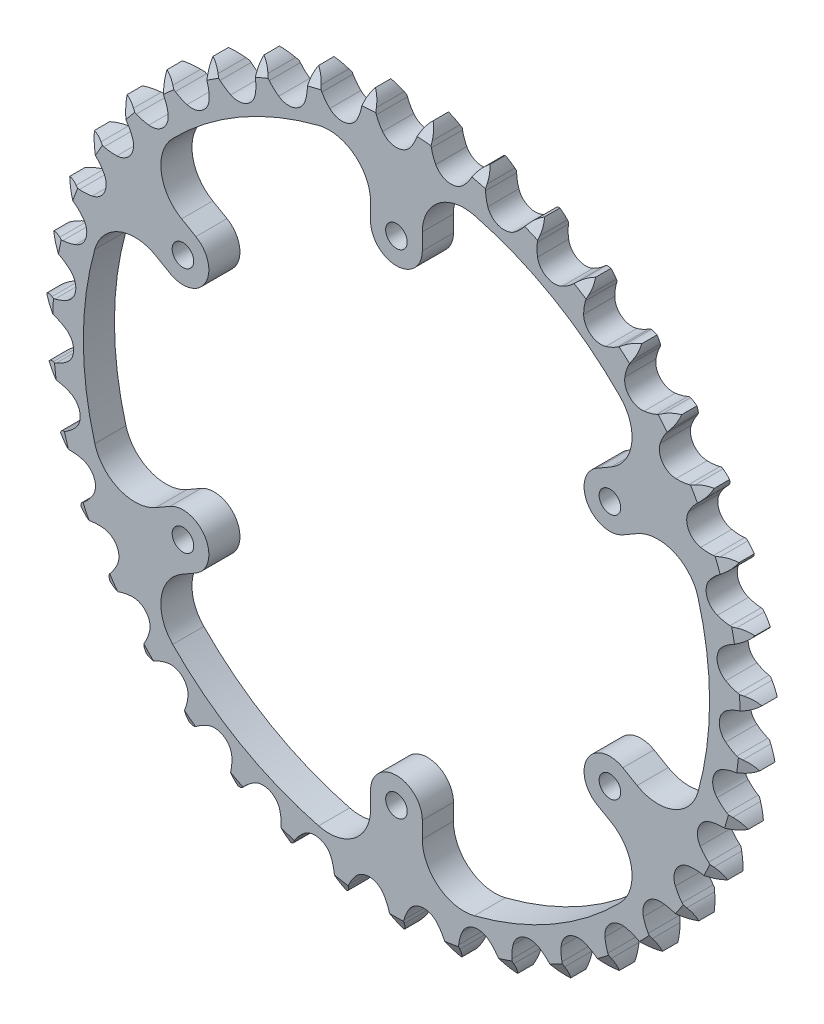
SolidWorks part; units mm, degrees
material "7075-T6 (SN)"
ref_plane "Front Plane" through (0, 0, 0) normal (0, 0, 1) x (1, 0, 0)
ref_plane "Top Plane" through (0, 0, 0) normal (0, 1, 0) x (1, 0, 0)
ref_plane "Right Plane" through (0, 0, 0) normal (1, 0, 0) x (0, 0, -1)
sketch "Work Sketch" plane through (0, 0, 0) normal (0, 0, 1) x (1, 0, 0)
  line L0 (0, 0) -> (0, 160.4542) construction
  line L1 (-112.0919, 78.9148) -> (87.2579, 78.9148) construction
  line L2 (5.102, 120.8822) -> (5.102, 112.9699) construction
  line L3 (-12.8497, 82.6953) -> (16.7256, 82.6953) construction
  line L4 (5.102, 82.6953) -> (-6.0879, 74.4036) construction
  line L5 (5.102, 82.6953) -> (-4.6505, 79.1506) construction
  line L6 (-4.6505, 79.1506) -> (-6.8863, 85.3019)
  line L7 (-11.5114, 78.0206) -> (-7.1525, 78.0206) construction
  line L8 (-11.0765, 124.7602) -> (-11.0765, 110.2345) construction
  line L9 (0, 0) -> (-3.4402, 42.6146) construction
  circle A0 centre (0, 0) radius 78.9148
  circle A1 centre (0, 78.9148) radius 4.0088
  arc A2 (-4.6505, 79.1506) -> (-3.2209, 76.5281) centre (5.0804, 82.7541) ccw
  circle A3 centre (-11.0765, 78.0206) radius 6.4254
  point P23 (-3.2209, 76.5281)
  dimension "D1" = 157.8295
  dimension "D8" = 10.3767
  dimension "D2" = 8.0177
  dimension "D3" = 5.102
  dimension "D4" = 3.7806
  dimension "D5" = 36.538
  dimension "D6" = 16.564
  dimension "D7" = 10.3767
  dimension "D9" = 0.8942
  dimension "D10" = 11.0765
  dimension "D11" = 4.615
sketch "Teeth Sketch" plane through (0, 0, 0) normal (0, 0, 1) x (1, 0, 0)
  line L0 (5.0376, 80.2155) -> (4.6505, 79.1506)
  line L1 (-7.4865, 92.7372) -> (-4.7839, 59.2593) construction
  line L2 (0, 0) -> (-10.9133, 132.3061) construction
  line L3 (7.8951, 79.9848) -> (8.1063, 78.8717)
  line L4 (16093.3137, -199351.4616) -> (-16096.7539, 199394.0762) construction
  line L5 (0, 146.3285) -> (0, 56.9858) construction
  line L6 (17.8398, 78.3686) -> (17.287, 77.3797)
  line L7 (0, -200000) -> (0, 200160.4542) construction
  line L8 (20.6234, 77.6826) -> (20.6533, 76.5499)
  line L9 (-4.6505, 79.1506) -> (-6.8863, 85.3019) construction
  line L10 (44.1616, 67.154) -> (43.8313, 66.0702)
  line L11 (-5.0376, 80.2155) -> (-4.6505, 79.1506)
  line L12 (30.18, 74.4921) -> (29.4757, 73.6046)
  line L13 (32.8175, 73.3684) -> (32.6653, 72.2456)
  line L14 (41.7385, 68.6862) -> (40.901, 67.9232)
  line L15 (52.2161, 61.1014) -> (51.267, 60.4826)
  line L16 (54.362, 59.2003) -> (53.8621, 58.1836)
  line L17 (61.3413, 51.9341) -> (60.3052, 51.4756)
  line L18 (63.1544, 49.7134) -> (62.4979, 48.79)
  line L19 (68.8777, 41.4218) -> (67.7815, 41.1354)
  line L20 (70.3112, 38.939) -> (69.515, 38.1328)
  line L21 (74.6303, 29.8366) -> (73.5023, 29.7298)
  line L22 (75.6469, 27.156) -> (74.7318, 26.488)
  line L23 (78.45, 17.4787) -> (77.3195, 17.5542)
  line L24 (79.0234, 14.6698) -> (78.013, 14.1572)
  line L25 (80.2378, 4.6681) -> (79.1341, 4.9239)
  line L26 (80.3533, 1.8035) -> (79.2737, 1.4597)
  line L27 (79.9476, -8.2634) -> (78.8992, -7.8338)
  line L28 (79.602, -11.1094) -> (78.4813, -11.2756)
  line L29 (77.5867, -20.9809) -> (76.6208, -20.3887)
  line L30 (76.7891, -23.7346) -> (75.6562, -23.7189)
  line L31 (73.2164, -33.155) -> (72.358, -32.4155)
  line L32 (71.9874, -35.7451) -> (70.8717, -35.5478)
  line L33 (66.9499, -44.4704) -> (66.2212, -43.6028)
  line L34 (65.3213, -46.8298) -> (64.2517, -46.4561)
  line L35 (58.9493, -54.634) -> (58.3693, -53.6608)
  line L36 (56.9634, -56.7016) -> (55.9676, -56.1612)
  line L37 (49.422, -63.3827) -> (49.0056, -62.329)
  line L38 (47.1301, -65.1049) -> (46.2339, -64.4118)
  line L39 (38.6147, -70.4897) -> (38.3727, -69.3829)
  line L40 (36.0763, -71.822) -> (35.3028, -70.9941)
  line L41 (26.8073, -75.7712) -> (26.746, -74.6398)
  line L42 (24.088, -76.679) -> (23.4574, -75.7377)
  line L43 (14.3056, -79.0901) -> (14.4266, -77.9636)
  line L44 (11.4759, -79.55) -> (11.0044, -78.5198)
  line L45 (1.4334, -80.3607) -> (1.7335, -79.2682)
  line L46 (-1.4334, -80.3607) -> (-1.7335, -79.2682)
  line L47 (-11.4759, -79.55) -> (-11.0044, -78.5198)
  line L48 (-14.3056, -79.0901) -> (-14.4266, -77.9636)
  line L49 (-24.088, -76.679) -> (-23.4574, -75.7377)
  line L50 (-26.8073, -75.7712) -> (-26.746, -74.6398)
  line L51 (-36.0763, -71.822) -> (-35.3028, -70.9941)
  line L52 (-38.6147, -70.4897) -> (-38.3727, -69.3829)
  line L53 (-47.1301, -65.1049) -> (-46.2339, -64.4118)
  line L54 (-49.422, -63.3827) -> (-49.0056, -62.329)
  line L55 (-56.9634, -56.7016) -> (-55.9676, -56.1612)
  line L56 (-58.9493, -54.634) -> (-58.3693, -53.6608)
  line L57 (-65.3213, -46.8298) -> (-64.2517, -46.4561)
  line L58 (-66.9499, -44.4704) -> (-66.2212, -43.6028)
  line L59 (-71.9874, -35.7451) -> (-70.8717, -35.5478)
  line L60 (-73.2164, -33.155) -> (-72.358, -32.4155)
  line L61 (-76.7891, -23.7346) -> (-75.6562, -23.7189)
  line L62 (-77.5867, -20.9809) -> (-76.6208, -20.3887)
  line L63 (-79.602, -11.1094) -> (-78.4813, -11.2756)
  line L64 (-79.9476, -8.2634) -> (-78.8992, -7.8338)
  line L65 (-80.3533, 1.8035) -> (-79.2737, 1.4597)
  line L66 (-80.2378, 4.6681) -> (-79.1341, 4.9239)
  line L67 (-79.0234, 14.6698) -> (-78.013, 14.1572)
  line L68 (-78.45, 17.4787) -> (-77.3195, 17.5542)
  line L69 (-75.6469, 27.156) -> (-74.7318, 26.488)
  line L70 (-74.6303, 29.8366) -> (-73.5023, 29.7298)
  line L71 (-70.3112, 38.939) -> (-69.515, 38.1328)
  line L72 (-68.8777, 41.4218) -> (-67.7815, 41.1354)
  line L73 (-63.1544, 49.7134) -> (-62.4979, 48.79)
  line L74 (-61.3413, 51.9341) -> (-60.3052, 51.4756)
  line L75 (-54.362, 59.2003) -> (-53.8621, 58.1836)
  line L76 (-52.2161, 61.1014) -> (-51.267, 60.4826)
  line L77 (-44.1616, 67.154) -> (-43.8313, 66.0702)
  line L78 (-41.7385, 68.6862) -> (-40.901, 67.9232)
  line L79 (-32.8175, 73.3684) -> (-32.6653, 72.2456)
  line L80 (-30.18, 74.4921) -> (-29.4757, 73.6046)
  line L81 (-20.6234, 77.6826) -> (-20.6533, 76.5499)
  line L82 (-17.8398, 78.3686) -> (-17.287, 77.3797)
  line L83 (-7.8951, 79.9848) -> (-8.1063, 78.8717)
  arc A0 (-6.8336, 82.8459) -> (-5.0376, 80.2155) centre (-11.0765, 78.0206) cw
  circle A1 centre (-11.0765, 78.0206) radius 6.4254 construction
  arc A2 (-3.2209, 76.5281) -> (-4.6505, 79.1506) centre (5.0804, 82.7541) cw
  arc A3 (-4.6505, 79.1506) -> (-3.2209, 76.5281) centre (5.0804, 82.7541) ccw construction
  circle A4 centre (0, 78.9148) radius 4.0088 construction
  arc A5 (-3.2209, 76.5281) -> (3.2209, 76.5281) centre (0, 78.9148) ccw
  arc A6 (3.2209, 76.5281) -> (4.6505, 79.1506) centre (-5.0804, 82.7541) ccw
  arc A7 (6.8336, 82.8459) -> (5.0376, 80.2155) centre (11.0765, 78.0206) ccw
  arc A8 (6.5443, 82.8692) -> (7.8951, 79.9848) centre (1.5824, 78.787) cw
  arc A9 (9.0967, 76.0537) -> (8.1063, 78.8717) centre (18.2893, 80.8676) cw
  arc A10 (9.0967, 76.0537) -> (15.4552, 75.0204) centre (12.6588, 77.8928) ccw
  arc A11 (15.4552, 75.0204) -> (17.287, 77.3797) centre (8.2601, 82.4975) ccw
  arc A12 (20.0345, 80.6769) -> (17.8398, 78.3686) centre (23.4484, 75.2334) ccw
  arc A13 (19.7528, 80.7463) -> (20.6234, 77.6826) centre (14.2002, 77.5129) cw
  arc A14 (21.1788, 73.6096) -> (20.6533, 76.5499) centre (31.0245, 76.8865) cw
  arc A15 (21.1788, 73.6096) -> (27.2892, 71.5697) centre (24.9898, 74.8535) ccw
  arc A16 (27.2892, 71.5697) -> (29.4757, 73.6046) centre (21.3867, 80.1041) ccw
  arc A17 (32.7165, 76.4184) -> (30.18, 74.4921) centre (35.2131, 70.4978) ccw
  arc A18 (32.4496, 76.5321) -> (32.8175, 73.3684) centre (26.4502, 74.2313) cw
  arc A19 (32.7124, 69.2591) -> (32.6653, 72.2456) centre (42.9562, 70.9142) cw
  arc A20 (32.7124, 69.2591) -> (38.4163, 66.2654) centre (36.6735, 69.8756) ccw
  arc A21 (38.4163, 66.2654) -> (40.901, 67.9232) centre (33.9593, 75.6361) ccw
  arc A22 (44.5512, 70.1807) -> (41.7385, 68.6862) centre (46.0657, 63.9363) ccw
  arc A23 (44.306, 70.3358) -> (44.1616, 67.154) centre (38.0153, 69.0271) cw
  arc A24 (43.3987, 63.1147) -> (43.8313, 66.0702) centre (53.7754, 63.1052) cw
  arc A25 (43.3987, 63.1147) -> (48.5486, 59.2448) centre (47.4074, 63.0878) ccw
  arc A26 (48.5486, 59.2448) -> (51.267, 60.4826) centre (45.6524, 69.2092) ccw
  arc A27 (55.2321, 62.1253) -> (52.2161, 61.1014) centre (55.7253, 55.7189) ccw
  arc A28 (55.0149, 62.3178) -> (54.362, 59.2003) centre (48.5957, 62.0351) cw
  arc A29 (52.961, 55.3358) -> (53.8621, 58.1836) centre (63.2018, 53.6618) cw
  arc A30 (52.961, 55.3358) -> (57.4234, 50.6899) centre (56.9135, 54.6662) ccw
  arc A31 (57.4234, 50.6899) -> (60.3052, 51.4756) centre (56.1632, 60.9898) ccw
  arc A32 (64.4824, 52.461) -> (61.3413, 51.9341) centre (63.9416, 46.0584) ccw
  arc A33 (64.2989, 52.6858) -> (63.1544, 49.7134) centre (57.9175, 53.4365) cw
  arc A34 (61.1517, 46.1237) -> (62.4979, 48.79) centre (70.9913, 42.8287) cw
  arc A35 (61.1517, 46.1237) -> (64.811, 40.8221) centre (64.9456, 44.8287) ccw
  arc A36 (64.811, 40.8221) -> (67.7815, 41.1354) centre (65.2193, 51.1908) ccw
  arc A37 (72.0627, 41.4379) -> (68.8777, 41.4218) centre (70.5018, 35.205) ccw
  arc A38 (71.9177, 41.6892) -> (70.3112, 38.939) centre (65.7393, 43.4539) cw
  arc A39 (67.7585, 35.717) -> (69.515, 38.1328) centre (76.9422, 30.8862) cw
  arc A40 (67.7585, 35.717) -> (70.5201, 29.8971) centre (71.2956, 33.8302) ccw
  arc A41 (70.5201, 29.8971) -> (73.5023, 29.7298) centre (72.5864, 40.0659) ccw
  arc A42 (77.7767, 29.3416) -> (74.6303, 29.8366) centre (75.2361, 23.4398) ccw
  arc A43 (77.6738, 29.6129) -> (75.6469, 27.156) centre (71.8585, 32.3458) cw
  arc A44 (72.6105, 24.3852) -> (74.7318, 26.488) centre (80.9003, 18.1439) cw
  arc A45 (72.6105, 24.3852) -> (74.4027, 18.1977) centre (75.7991, 21.9555) ccw
  arc A46 (74.4027, 18.1977) -> (77.3195, 17.5542) centre (78.0734, 27.9034) ccw
  arc A47 (81.4762, 16.4854) -> (78.45, 17.4787) centre (78.0218, 11.0675) ccw
  arc A48 (81.4182, 16.7697) -> (79.0234, 14.6698) centre (76.1166, 20.4) cw
  arc A49 (75.5818, 12.4219) -> (78.013, 14.1572) centre (82.7631, 4.9316) cw
  arc A50 (75.5818, 12.4219) -> (76.3583, 6.027) centre (78.3394, 9.5121) ccw
  arc A51 (76.3583, 6.027) -> (79.1341, 4.9239) centre (81.5384, 15.0182) ccw
  arc A52 (83.0656, 3.2022) -> (80.2378, 4.6681) centre (78.7868, -1.5914) ccw
  arc A53 (83.0539, 3.4922) -> (80.3533, 1.8035) centre (78.4033, 7.9259) cw
  arc A54 (76.5957, 0.1368) -> (79.2737, 1.4597) centre (82.4825, -8.4084) cw
  arc A55 (76.5957, 0.1368) -> (76.3363, -6.2998) centre (78.8508, -3.1776) ccw
  arc A56 (76.3363, -6.2998) -> (78.8992, -7.8338) centre (82.8916, 1.7441) ccw
  arc A57 (82.5035, -10.1639) -> (79.9476, -8.2634) centre (77.5113, -14.2091) ccw
  arc A58 (82.5385, -9.8758) -> (79.602, -11.1094) centre (78.6594, -4.7535) cw
  arc A59 (75.6257, -12.1517) -> (78.4813, -11.2756) centre (80.0655, -21.5307) cw
  arc A60 (75.6257, -12.1517) -> (74.3372, -18.4634) centre (77.3199, -15.785) ccw
  arc A61 (74.3372, -18.4634) -> (76.6208, -20.3887) centre (82.0979, -11.5753) ccw
  arc A62 (79.8047, -23.2668) -> (77.5867, -20.9809) centre (74.2283, -26.4587) ccw
  arc A63 (79.8855, -22.9881) -> (76.7891, -23.7346) centre (76.8783, -17.3098) cw
  arc A64 (72.6971, -24.1256) -> (75.6562, -23.7189) centre (75.5749, -34.0953) cw
  arc A65 (72.6971, -24.1256) -> (70.4128, -30.1488) centre (73.7866, -27.9836) ccw
  arc A66 (70.4128, -30.1488) -> (72.358, -32.4155) centre (79.178, -24.5948) ccw
  arc A67 (75.039, -35.7671) -> (73.2164, -33.155) centre (69.0227, -38.0232) ccw
  arc A68 (75.1634, -35.5049) -> (71.9874, -35.7451) centre (73.106, -29.4178) cw
  arc A69 (67.8857, -35.4746) -> (70.8717, -35.5478) centre (69.127, -45.7768) cw
  arc A70 (67.8857, -35.4746) -> (64.6648, -41.0534) centre (68.3422, -39.4574) ccw
  arc A71 (64.6648, -41.0534) -> (66.2212, -43.6028) centre (74.2074, -36.9773) ccw
  arc A72 (68.3299, -47.341) -> (66.9499, -44.4704) centre (62.0296, -48.6028) ccw
  arc A73 (68.4947, -47.1022) -> (65.3213, -46.8298) centre (67.4404, -40.7639) cw
  arc A74 (61.3161, -45.9049) -> (64.2517, -46.4561) centre (60.8887, -56.2728) cw
  arc A75 (61.3161, -45.9049) -> (57.2419, -50.8948) centre (61.1278, -49.9093) ccw
  arc A76 (57.2419, -50.8948) -> (58.3693, -53.6608) centre (67.3148, -48.4022) ccw
  arc A77 (59.851, -57.6888) -> (58.9493, -54.634) centre (53.4299, -57.9236) ccw
  arc A78 (60.052, -57.4796) -> (56.9634, -56.7016) centre (60.0281, -51.0542) cw
  arc A79 (53.1584, -55.1462) -> (55.9676, -56.1612) centre (51.0734, -65.3113) cw
  arc A80 (53.1584, -55.1462) -> (48.3366, -59.4179) centre (52.3302, -59.0685) ccw
  arc A81 (48.3366, -59.4179) -> (49.0056, -62.329) centre (58.6789, -58.5735) ccw
  arc A82 (49.822, -66.5425) -> (49.422, -63.3827) centre (43.4464, -65.7443) ccw
  arc A83 (50.054, -66.3682) -> (47.1301, -65.1049) centre (51.0611, -60.0222) cw
  arc A84 (43.6239, -62.9593) -> (46.2339, -64.4118) centre (39.9354, -72.6583) cw
  arc A85 (43.6239, -62.9593) -> (38.1793, -66.4022) centre (42.1772, -66.698) ccw
  arc A86 (38.1793, -66.4022) -> (38.3727, -69.3829) centre (48.5231, -67.2277) ccw
  arc A87 (38.5026, -73.6728) -> (38.6147, -70.4897) centre (32.3376, -71.8622) ccw
  arc A88 (38.7596, -73.538) -> (36.0763, -71.822) centre (40.7716, -67.4357) cw
  arc A89 (32.9596, -69.1417) -> (35.3028, -70.9941) centre (27.763, -78.1234) cw
  arc A90 (32.9596, -69.1417) -> (27.0333, -71.6667) centre (30.932, -72.6) ccw
  arc A91 (27.0333, -71.6667) -> (26.746, -74.6398) centre (37.1107, -74.1408) ccw
  arc A92 (26.1861, -78.8951) -> (26.8073, -75.7712) centre (20.3913, -76.1189) ccw
  arc A93 (26.4613, -78.8032) -> (24.088, -76.679) centre (29.4261, -73.1027) cw
  arc A94 (21.4417, -73.5335) -> (23.4574, -75.7377) centre (14.8716, -81.5653) cw
  arc A95 (21.4417, -73.5335) -> (15.187, -75.0751) centre (18.8855, -76.6216) ccw
  arc A96 (15.187, -75.0751) -> (14.4266, -77.9636) centre (24.7371, -79.1336) ccw
  arc A97 (13.1913, -82.0739) -> (14.3056, -79.0901) centre (7.9169, -78.4042) ccw
  arc A98 (13.4777, -82.0274) -> (11.4759, -79.55) centre (17.3186, -76.8763) cw
  arc A99 (9.3684, -76.0207) -> (11.0044, -78.5198) centre (1.595, -82.8946) cw
  arc A100 (9.3684, -76.0207) -> (2.9475, -76.5391) centre (6.35, -78.6589) ccw
  arc A101 (2.9475, -76.5391) -> (1.7335, -79.2682) centre (11.7228, -82.077) ccw
  arc A102 (-0.1451, -83.1271) -> (1.4334, -80.3607) centre (-4.7625, -78.6589) ccw
  arc A103 (0.1451, -83.1271) -> (-1.4334, -80.3607) centre (4.7625, -78.6589) cw
  arc A104 (-2.9475, -76.5391) -> (-1.7335, -79.2682) centre (-11.7228, -82.077) cw
  arc A105 (-2.9475, -76.5391) -> (-9.3684, -76.0207) centre (-6.35, -78.6589) ccw
  arc A106 (-9.3684, -76.0207) -> (-11.0044, -78.5198) centre (-1.595, -82.8946) ccw
  arc A107 (-13.4777, -82.0274) -> (-11.4759, -79.55) centre (-17.3186, -76.8763) ccw
  arc A108 (-13.1913, -82.0739) -> (-14.3056, -79.0901) centre (-7.9169, -78.4042) cw
  arc A109 (-15.187, -75.0751) -> (-14.4266, -77.9636) centre (-24.7371, -79.1336) cw
  arc A110 (-15.187, -75.0751) -> (-21.4417, -73.5335) centre (-18.8855, -76.6216) ccw
  arc A111 (-21.4417, -73.5335) -> (-23.4574, -75.7377) centre (-14.8716, -81.5653) ccw
  arc A112 (-26.4613, -78.8032) -> (-24.088, -76.679) centre (-29.4261, -73.1027) ccw
  arc A113 (-26.1861, -78.8951) -> (-26.8073, -75.7712) centre (-20.3913, -76.1189) cw
  arc A114 (-27.0333, -71.6667) -> (-26.746, -74.6398) centre (-37.1107, -74.1408) cw
  arc A115 (-27.0333, -71.6667) -> (-32.9596, -69.1417) centre (-30.932, -72.6) ccw
  arc A116 (-32.9596, -69.1417) -> (-35.3028, -70.9941) centre (-27.763, -78.1234) ccw
  arc A117 (-38.7596, -73.538) -> (-36.0763, -71.822) centre (-40.7716, -67.4357) ccw
  arc A118 (-38.5026, -73.6728) -> (-38.6147, -70.4897) centre (-32.3376, -71.8622) cw
  arc A119 (-38.1793, -66.4022) -> (-38.3727, -69.3829) centre (-48.5231, -67.2277) cw
  arc A120 (-38.1793, -66.4022) -> (-43.6239, -62.9593) centre (-42.1772, -66.698) ccw
  arc A121 (-43.6239, -62.9593) -> (-46.2339, -64.4118) centre (-39.9354, -72.6583) ccw
  arc A122 (-50.054, -66.3682) -> (-47.1301, -65.1049) centre (-51.0611, -60.0222) ccw
  arc A123 (-49.822, -66.5425) -> (-49.422, -63.3827) centre (-43.4464, -65.7443) cw
  arc A124 (-48.3366, -59.4179) -> (-49.0056, -62.329) centre (-58.6789, -58.5735) cw
  arc A125 (-48.3366, -59.4179) -> (-53.1584, -55.1462) centre (-52.3302, -59.0685) ccw
  arc A126 (-53.1584, -55.1462) -> (-55.9676, -56.1612) centre (-51.0734, -65.3113) ccw
  arc A127 (-60.052, -57.4796) -> (-56.9634, -56.7016) centre (-60.0281, -51.0542) ccw
  arc A128 (-59.851, -57.6888) -> (-58.9493, -54.634) centre (-53.4299, -57.9236) cw
  arc A129 (-57.2419, -50.8948) -> (-58.3693, -53.6608) centre (-67.3148, -48.4022) cw
  arc A130 (-57.2419, -50.8948) -> (-61.3161, -45.9049) centre (-61.1278, -49.9093) ccw
  arc A131 (-61.3161, -45.9049) -> (-64.2517, -46.4561) centre (-60.8887, -56.2728) ccw
  arc A132 (-68.4947, -47.1022) -> (-65.3213, -46.8298) centre (-67.4404, -40.7639) ccw
  arc A133 (-68.3299, -47.341) -> (-66.9499, -44.4704) centre (-62.0296, -48.6028) cw
  arc A134 (-64.6648, -41.0534) -> (-66.2212, -43.6028) centre (-74.2074, -36.9773) cw
  arc A135 (-64.6648, -41.0534) -> (-67.8857, -35.4746) centre (-68.3422, -39.4574) ccw
  arc A136 (-67.8857, -35.4746) -> (-70.8717, -35.5478) centre (-69.127, -45.7768) ccw
  arc A137 (-75.1634, -35.5049) -> (-71.9874, -35.7451) centre (-73.106, -29.4178) ccw
  arc A138 (-75.039, -35.7671) -> (-73.2164, -33.155) centre (-69.0227, -38.0232) cw
  arc A139 (-70.4128, -30.1488) -> (-72.358, -32.4155) centre (-79.178, -24.5948) cw
  arc A140 (-70.4128, -30.1488) -> (-72.6971, -24.1256) centre (-73.7866, -27.9836) ccw
  arc A141 (-72.6971, -24.1256) -> (-75.6562, -23.7189) centre (-75.5749, -34.0953) ccw
  arc A142 (-79.8855, -22.9881) -> (-76.7891, -23.7346) centre (-76.8783, -17.3098) ccw
  arc A143 (-79.8047, -23.2668) -> (-77.5867, -20.9809) centre (-74.2283, -26.4587) cw
  arc A144 (-74.3372, -18.4634) -> (-76.6208, -20.3887) centre (-82.0979, -11.5753) cw
  arc A145 (-74.3372, -18.4634) -> (-75.6257, -12.1517) centre (-77.3199, -15.785) ccw
  arc A146 (-75.6257, -12.1517) -> (-78.4813, -11.2756) centre (-80.0655, -21.5307) ccw
  arc A147 (-82.5385, -9.8758) -> (-79.602, -11.1094) centre (-78.6594, -4.7535) ccw
  arc A148 (-82.5035, -10.1639) -> (-79.9476, -8.2634) centre (-77.5113, -14.2091) cw
  arc A149 (-76.3363, -6.2998) -> (-78.8992, -7.8338) centre (-82.8916, 1.7441) cw
  arc A150 (-76.3363, -6.2998) -> (-76.5957, 0.1368) centre (-78.8508, -3.1776) ccw
  arc A151 (-76.5957, 0.1368) -> (-79.2737, 1.4597) centre (-82.4825, -8.4084) ccw
  arc A152 (-83.0539, 3.4922) -> (-80.3533, 1.8035) centre (-78.4033, 7.9259) ccw
  arc A153 (-83.0656, 3.2022) -> (-80.2378, 4.6681) centre (-78.7868, -1.5914) cw
  arc A154 (-76.3583, 6.027) -> (-79.1341, 4.9239) centre (-81.5384, 15.0182) cw
  arc A155 (-76.3583, 6.027) -> (-75.5818, 12.4219) centre (-78.3394, 9.5121) ccw
  arc A156 (-75.5818, 12.4219) -> (-78.013, 14.1572) centre (-82.7631, 4.9316) ccw
  arc A157 (-81.4182, 16.7697) -> (-79.0234, 14.6698) centre (-76.1166, 20.4) ccw
  arc A158 (-81.4762, 16.4854) -> (-78.45, 17.4787) centre (-78.0218, 11.0675) cw
  arc A159 (-74.4027, 18.1977) -> (-77.3195, 17.5542) centre (-78.0734, 27.9034) cw
  arc A160 (-74.4027, 18.1977) -> (-72.6105, 24.3852) centre (-75.7991, 21.9555) ccw
  arc A161 (-72.6105, 24.3852) -> (-74.7318, 26.488) centre (-80.9003, 18.1439) ccw
  arc A162 (-77.6738, 29.6129) -> (-75.6469, 27.156) centre (-71.8585, 32.3458) ccw
  arc A163 (-77.7767, 29.3416) -> (-74.6303, 29.8366) centre (-75.2361, 23.4398) cw
  arc A164 (-70.5201, 29.8971) -> (-73.5023, 29.7298) centre (-72.5864, 40.0659) cw
  arc A165 (-70.5201, 29.8971) -> (-67.7585, 35.717) centre (-71.2956, 33.8302) ccw
  arc A166 (-67.7585, 35.717) -> (-69.515, 38.1328) centre (-76.9422, 30.8862) ccw
  arc A167 (-71.9177, 41.6892) -> (-70.3112, 38.939) centre (-65.7393, 43.4539) ccw
  arc A168 (-72.0627, 41.4379) -> (-68.8777, 41.4218) centre (-70.5018, 35.205) cw
  arc A169 (-64.811, 40.8221) -> (-67.7815, 41.1354) centre (-65.2193, 51.1908) cw
  arc A170 (-64.811, 40.8221) -> (-61.1517, 46.1237) centre (-64.9456, 44.8287) ccw
  arc A171 (-61.1517, 46.1237) -> (-62.4979, 48.79) centre (-70.9913, 42.8287) ccw
  arc A172 (-64.2989, 52.6858) -> (-63.1544, 49.7134) centre (-57.9175, 53.4365) ccw
  arc A173 (-64.4824, 52.461) -> (-61.3413, 51.9341) centre (-63.9416, 46.0584) cw
  arc A174 (-57.4234, 50.6899) -> (-60.3052, 51.4756) centre (-56.1632, 60.9898) cw
  arc A175 (-57.4234, 50.6899) -> (-52.961, 55.3358) centre (-56.9135, 54.6662) ccw
  arc A176 (-52.961, 55.3358) -> (-53.8621, 58.1836) centre (-63.2018, 53.6618) ccw
  arc A177 (-55.0149, 62.3178) -> (-54.362, 59.2003) centre (-48.5957, 62.0351) ccw
  arc A178 (-55.2321, 62.1253) -> (-52.2161, 61.1014) centre (-55.7253, 55.7189) cw
  arc A179 (-48.5486, 59.2448) -> (-51.267, 60.4826) centre (-45.6524, 69.2092) cw
  arc A180 (-48.5486, 59.2448) -> (-43.3987, 63.1147) centre (-47.4074, 63.0878) ccw
  arc A181 (-43.3987, 63.1147) -> (-43.8313, 66.0702) centre (-53.7754, 63.1052) ccw
  arc A182 (-44.306, 70.3358) -> (-44.1616, 67.154) centre (-38.0153, 69.0271) ccw
  arc A183 (-44.5512, 70.1807) -> (-41.7385, 68.6862) centre (-46.0657, 63.9363) cw
  arc A184 (-38.4163, 66.2654) -> (-40.901, 67.9232) centre (-33.9593, 75.6361) cw
  arc A185 (-38.4163, 66.2654) -> (-32.7124, 69.2591) centre (-36.6735, 69.8756) ccw
  arc A186 (-32.7124, 69.2591) -> (-32.6653, 72.2456) centre (-42.9562, 70.9142) ccw
  arc A187 (-32.4496, 76.5321) -> (-32.8175, 73.3684) centre (-26.4502, 74.2313) ccw
  arc A188 (-32.7165, 76.4184) -> (-30.18, 74.4921) centre (-35.2131, 70.4978) cw
  arc A189 (-27.2892, 71.5697) -> (-29.4757, 73.6046) centre (-21.3867, 80.1041) cw
  arc A190 (-27.2892, 71.5697) -> (-21.1788, 73.6096) centre (-24.9898, 74.8535) ccw
  arc A191 (-21.1788, 73.6096) -> (-20.6533, 76.5499) centre (-31.0245, 76.8865) ccw
  arc A192 (-19.7528, 80.7463) -> (-20.6234, 77.6826) centre (-14.2002, 77.5129) ccw
  arc A193 (-20.0345, 80.6769) -> (-17.8398, 78.3686) centre (-23.4484, 75.2334) cw
  arc A194 (-15.4552, 75.0204) -> (-17.287, 77.3797) centre (-8.2601, 82.4975) cw
  arc A195 (-15.4552, 75.0204) -> (-9.0967, 76.0537) centre (-12.6588, 77.8928) ccw
  arc A196 (-9.0967, 76.0537) -> (-8.1063, 78.8717) centre (-18.2893, 80.8676) ccw
  arc A197 (-6.5443, 82.8692) -> (-7.8951, 79.9848) centre (-1.5824, 78.787) ccw
  point P77 (0, 0)
  dimension "D1" = 4.615
  dimension "D2" = 4.715
  dimension "D3" = 39
extrude "Extrusion" add sketch "Teeth Sketch" along normal blind 7.2136 contours A0 region at (0, 0, 0)
sketch "Sketch1" plane through (0, 0, 0) normal (0, 0, -1) x (-1, 0, 0)
  circle A0 centre (0, 0) radius 78.9443
  circle A1 centre (0, 0) radius 72.5943
  dimension "D1" = 6.35
extrude "Cut-Extrude" cut sketch "Sketch1" against normal through all both and the other way through all contours A1
ref_axis "Axis1" through (0, 0, 7.2136) along (0, 0, -1)
ref_plane "Sprocket Center Plane" through (0, 0, 3.6068) normal (0, 0, 1) x (1, 0, 0)
sketch "Pitch Circle" plane through (0, 0, 3.6068) normal (0, 0, -1) x (-1, 0, 0)
  circle A0 centre (0, 0) radius 78.9148 construction
  dimension "D1" = 157.8295
sketch "Chain Pitch Circle" plane through (0, 0, 0) normal (0, 0, -1) x (-1, 0, 0)
  circle A0 centre (0, 0) radius 78.9148 construction
  dimension "D1" = 157.8295
ref_plane "Center Plane" through (0, 0, 3.6068) normal (0, 0, 1) x (1, 0, 0)
sketch "Sketch2" plane through (0, 0, 0) normal (0, 0, -1) x (-1, 0, 0)
  line L0 (6, 57.15) -> (6, 72.3459)
  line L2 (-6, 57.15) -> (-6, 72.3459)
  circle A0 centre (0, 0) radius 57.15 construction
  circle A1 centre (0, 57.15) radius 6
  circle A4 centre (0, 0) radius 72.5943
  circle A5 centre (0, 0) radius 72.5943 construction
  arc A10 (18.0522, 70.3139) -> (6, 60.9651) centre (15.652, 60.9651) ccw
  arc A11 (-6, 60.9651) -> (-18.0522, 70.3139) centre (-15.652, 60.9651) ccw
  dimension "D1" = 114.3
  dimension "D2" = 12
  dimension "D3" = 9.652
extrude "Boss-Extrude" add sketch "Sketch2" against normal up to surface (7.2136 mm away) contours A1 | A4 A1 | A10 A4 L0 | A11 L2 A4 region at (0, 67.103, 0) region at (0, 57.15, 0) region at (-8.7722, 69.444, 0) region at (8.7722, 69.444, 0) up to face at (-72.5943, 0, 7.2136)
hole_wizard "M5 Counter Bore" positions "Sketch3" profile "Sketch4" hole size "Ø5.0" standard "ANSI Metric" end condition through all
sketch "Sketch3" plane through (0, 0, 0) normal (0, 0, -1) x (-1, 0, 0)
  point P0 (0, 57.15)
sketch "Sketch4" plane through (0, 57.15, 0) normal (1, 0, 0) x (0, 1, 0)
  line L0 (0, 0) -> (0, 7.2136)
  line L1 (0, 7.2136) -> (2.5, 7.2136)
  line L2 (2.5, 7.2136) -> (2.5, 0)
  line L5 (2.5, 0) -> (0, 0)
  line L11 (0, -6.35) -> (0, 107.95) construction
  dimension "Thru Hole Dia." = 5
  dimension "Thru Hole Depth" = 7.2136
pattern_circular "Bolt Hole Pattern" count 6 over 360 about axis through (0, 0, 0) along (0, 0, 1) of "M5 Counter Bore", "Boss-Extrude"
sketch "Sketch5" plane through (0, 0, 0) normal (1, 0, 0) x (0, 0, -1)
  line L0 (-1.8288, -82.9722) -> (-5.3848, -82.9722)
  line L1 (-7.2136, -81.8977) -> (0, -81.8977) construction
  line L2 (-5.3848, -82.9722) -> (-5.3848, -79.6702)
  line L3 (-5.3848, -79.6702) -> (-7.2136, -79.6702)
  line L4 (-7.2136, -79.6702) -> (-5.3848, -82.9722)
  line L5 (-7.2136, -79.6702) -> (-7.2136, -82.9722)
  line L6 (-7.2136, -82.9722) -> (-5.3848, -82.9722)
  line L9 (-7.2136, -82.9722) -> (0, -82.9722) construction
  point P5 (-3.6068, -81.8977)
  dimension "D1" = 3.556
  dimension "D2" = 3.302
  dimension "D3" = 28.98
  dimension "D4" = 1.8288
revolve "Cut-Revolve1" cut sketch "Sketch5" angle 360 about axis through (0, 0, 7.2136) along (0, 0, -1) region at (0, -81.8715, 6.604)
mirror "Mirror1" about plane through (0, 0, 3.6068) normal (0, 0, 1) of "Cut-Revolve1"
sketch "Sketch6" plane through (0, 0, 0) normal (0, 0, 1) x (1, 0, 0)
  circle A0 centre (0, 57.15) radius 5
  dimension "D1" = 10
extrude "Cut-Extrude1" cut sketch "Sketch6" along normal blind 1.5 contours A0
pattern_circular "CirPattern1" count 6 over 360 about axis through (0, 0, 0) along (0, 0, 1) of "Cut-Extrude1"
split line "Split Line1" [suppressed]
ref_point "Point1" [suppressed]
ref_point "Point2" [suppressed]
ref_point "Point3" [suppressed]
ref_point "Point4" [suppressed]
ref_point "Point5" [suppressed]
ref_point "Point6" [suppressed]
ref_plane "Plane1" [suppressed] through (49.4934, 0, 0) normal (1, 0, 0) x (0, 0, -1)
split line "Split Line2" [suppressed]
ref_plane "Plane2" [suppressed] through (-49.4934, 0, 0) normal (1, 0, 0) x (0, 0, -1)
split line "Split Line3" [suppressed]
sketch "Sketch7" [suppressed] plane through (0, 0, 7.2136) normal (0, 0, 1) x (1, 0, 0)
  arc A0 (52.4934, -23.3788) -> (46.4934, -33.7712) centre (49.4934, -28.575) ccw construction
  arc A1 (6, -57.15) -> (-6, -57.15) centre (0, -57.15) ccw construction
  arc A2 (-46.4934, -33.7712) -> (-52.4934, -23.3788) centre (-49.4934, -28.575) ccw construction
  arc A3 (-52.4934, 23.3788) -> (-46.4934, 33.7712) centre (-49.4934, 28.575) ccw construction
  arc A4 (46.4934, 33.7712) -> (52.4934, 23.3788) centre (49.4934, 28.575) ccw construction
  arc A5 (-6, 57.15) -> (6, 57.15) centre (0, 57.15) ccw construction
  arc A6 (52.4934, -23.3788) -> (46.4934, -33.7712) centre (49.4934, -28.575) ccw
  arc A7 (6, -57.15) -> (-6, -57.15) centre (0, -57.15) ccw
  arc A8 (-46.4934, -33.7712) -> (-52.4934, -23.3788) centre (-49.4934, -28.575) ccw
  arc A9 (-52.4934, 23.3788) -> (-46.4934, 33.7712) centre (-49.4934, 28.575) ccw
  arc A10 (46.4934, 33.7712) -> (52.4934, 23.3788) centre (49.4934, 28.575) ccw
  arc A11 (-6, 57.15) -> (6, 57.15) centre (0, 57.15) ccw
  circle A12 centre (-49.4934, 28.575) radius 6
  circle A13 centre (0, 57.15) radius 6
  circle A14 centre (49.4934, 28.575) radius 6
  circle A15 centre (0, -57.15) radius 6
  circle A16 centre (-49.4934, -28.575) radius 6
  circle A17 centre (49.4934, -28.575) radius 6
split line "Split Line4" [suppressed]
sketch "Sketch8" [suppressed] plane through (0, 0, 0) normal (0, 0, -1) x (-1, 0, 0)
  line L78 (4.4388, 80.0552) -> (4.1736, 79.3256)
  line L79 (4.4388, 80.0552) -> (4.1736, 79.3256)
  line L80 (-4.1736, 79.3256) -> (-4.4388, 80.0552)
  line L81 (-4.1736, 79.3256) -> (-4.4388, 80.0552)
  line L82 (-8.4604, 79.7305) -> (-8.6051, 78.9679)
  line L83 (-8.4604, 79.7305) -> (-8.6051, 78.9679)
  line L84 (-16.8443, 77.6289) -> (-17.2231, 78.3065)
  line L85 (-16.8443, 77.6289) -> (-17.2231, 78.3065)
  line L86 (-21.1406, 77.3409) -> (-21.1611, 76.5649)
  line L87 (-21.1406, 77.3409) -> (-21.1611, 76.5649)
  line L88 (-29.0787, 73.9216) -> (-29.5613, 74.5296)
  line L89 (-29.0787, 73.9216) -> (-29.5613, 74.5296)
  line L90 (-33.2731, 72.9482) -> (-33.1689, 72.1789)
  line L91 (-33.2731, 72.9482) -> (-33.1689, 72.1789)
  line L92 (-40.56, 68.2998) -> (-41.1339, 68.8225)
  line L93 (-40.56, 68.2998) -> (-41.1339, 68.8225)
  line L94 (-44.544, 66.6661) -> (-44.3177, 65.9236)
  line L95 (-44.544, 66.6661) -> (-44.3177, 65.9236)
  line L96 (-50.9908, 60.909) -> (-51.6411, 61.333)
  line L97 (-50.9908, 60.909) -> (-51.6411, 61.333)
  line L98 (-54.6611, 58.6575) -> (-54.3187, 57.9608)
  line L99 (-54.6611, 58.6575) -> (-54.3187, 57.9608)
  line L100 (-60.101, 51.9408) -> (-60.8109, 52.2549)
  line L101 (-60.101, 51.9408) -> (-60.8109, 52.2549)
  line L102 (-63.3626, 49.1296) -> (-62.9128, 48.4969)
  line L103 (-63.3626, 49.1296) -> (-62.9128, 48.4969)
  line L104 (-67.6546, 41.6273) -> (-68.4057, 41.8235)
  line L105 (-67.6546, 41.6273) -> (-68.4057, 41.8235)
  line L106 (-70.423, 38.3293) -> (-69.8776, 37.777)
  line L107 (-70.423, 38.3293) -> (-69.8776, 37.777)
  line L108 (-73.456, 30.2356) -> (-74.2288, 30.3088)
  line L109 (-73.456, 30.2356) -> (-74.2288, 30.3088)
  line L110 (-75.6595, 26.5363) -> (-75.0325, 26.0786)
  line L111 (-75.6595, 26.5363) -> (-75.0325, 26.0786)
  line L112 (-77.3549, 18.0609) -> (-78.1294, 18.0092)
  line L113 (-77.3549, 18.0609) -> (-78.1294, 18.0092)
  line L114 (-78.9365, 14.056) -> (-78.2442, 13.7048)
  line L115 (-78.9365, 14.056) -> (-78.2442, 13.7048)
  line L116 (-79.2503, 5.4185) -> (-80.0065, 5.2432)
  line L117 (-79.2503, 5.4185) -> (-80.0065, 5.2432)
  line L118 (-80.169, 1.2117) -> (-79.4294, 0.9761)
  line L119 (-80.169, 1.2117) -> (-79.4294, 0.9761)
  line L120 (-79.0932, -7.3644) -> (-79.8115, -7.6587)
  line L121 (-79.0932, -7.3644) -> (-79.8115, -7.6587)
  line L122 (-79.3252, -11.664) -> (-78.5573, -11.7779)
  line L123 (-79.3252, -11.664) -> (-78.5573, -11.7779)
  line L124 (-76.8877, -19.9564) -> (-77.5495, -20.3622)
  line L125 (-76.8877, -19.9564) -> (-77.5495, -20.3622)
  line L126 (-76.4269, -24.2376) -> (-75.6507, -24.2268)
  line L127 (-76.4269, -24.2376) -> (-75.6507, -24.2268)
  line L128 (-72.6908, -32.0317) -> (-73.2789, -32.5383)
  line L129 (-72.6908, -32.0317) -> (-73.2789, -32.5383)
  line L130 (-71.5492, -36.1835) -> (-70.7848, -36.0483)
  line L131 (-71.5492, -36.1835) -> (-70.7848, -36.0483)
  line L132 (-66.6112, -43.2773) -> (-67.1104, -43.8717)
  line L133 (-66.6112, -43.2773) -> (-67.1104, -43.8717)
  line L134 (-64.8184, -47.1922) -> (-64.0856, -46.9362)
  line L135 (-64.8184, -47.1922) -> (-64.0856, -46.9362)
  line L136 (-58.8064, -53.402) -> (-59.2039, -54.0688)
  line L137 (-58.8064, -53.402) -> (-59.2039, -54.0688)
  line L138 (-56.4089, -56.9787) -> (-55.7266, -56.6085)
  line L139 (-56.4089, -56.9787) -> (-55.7266, -56.6085)
  line L140 (-49.4786, -62.1437) -> (-49.7639, -62.8656)
  line L141 (-49.4786, -62.1437) -> (-49.7639, -62.8656)
  line L142 (-46.5384, -65.2895) -> (-45.9243, -64.8146)
  line L143 (-46.5384, -65.2895) -> (-45.9243, -64.8146)
  line L144 (-38.8693, -69.2759) -> (-39.0351, -70.0342)
  line L145 (-38.8693, -69.2759) -> (-39.0351, -70.0342)
  line L146 (-35.4626, -71.9093) -> (-34.9326, -71.342)
  line L147 (-35.4626, -71.9093) -> (-34.9326, -71.342)
  line L148 (-27.2533, -74.6139) -> (-27.2954, -75.389)
  line L149 (-27.2533, -74.6139) -> (-27.2954, -75.389)
  line L150 (-23.4683, -76.6667) -> (-23.0362, -76.0218)
  line L151 (-23.4683, -76.6667) -> (-23.0362, -76.0218)
  line L152 (-14.9315, -78.0194) -> (-14.8487, -78.7912)
  line L153 (-14.9315, -78.0194) -> (-14.8487, -78.7912)
  line L154 (-10.8662, -79.4384) -> (-10.5432, -78.7326)
  line L155 (-10.8662, -79.4384) -> (-10.5432, -78.7326)
  line L156 (-2.223, -79.4042) -> (-2.0174, -80.1528)
  line L157 (-2.223, -79.4042) -> (-2.0174, -80.1528)
  line L158 (2.0174, -80.1528) -> (2.223, -79.4042)
  line L159 (2.0174, -80.1528) -> (2.223, -79.4042)
  line L160 (10.5432, -78.7326) -> (10.8662, -79.4384)
  line L161 (10.5432, -78.7326) -> (10.8662, -79.4384)
  line L162 (14.8487, -78.7912) -> (14.9315, -78.0194)
  line L163 (14.8487, -78.7912) -> (14.9315, -78.0194)
  line L164 (23.0362, -76.0218) -> (23.4683, -76.6667)
  line L165 (23.0362, -76.0218) -> (23.4683, -76.6667)
  line L166 (27.2954, -75.389) -> (27.2533, -74.6139)
  line L167 (27.2954, -75.389) -> (27.2533, -74.6139)
  line L168 (34.9326, -71.342) -> (35.4626, -71.9093)
  line L169 (34.9326, -71.342) -> (35.4626, -71.9093)
  line L170 (39.0351, -70.0342) -> (38.8693, -69.2759)
  line L171 (39.0351, -70.0342) -> (38.8693, -69.2759)
  line L172 (45.9243, -64.8146) -> (46.5384, -65.2895)
  line L173 (45.9243, -64.8146) -> (46.5384, -65.2895)
  line L174 (49.7639, -62.8656) -> (49.4786, -62.1437)
  line L175 (49.7639, -62.8656) -> (49.4786, -62.1437)
  line L176 (55.7266, -56.6085) -> (56.4089, -56.9787)
  line L177 (55.7266, -56.6085) -> (56.4089, -56.9787)
  line L178 (59.2039, -54.0688) -> (58.8064, -53.402)
  line L179 (59.2039, -54.0688) -> (58.8064, -53.402)
  line L180 (64.0856, -46.9362) -> (64.8184, -47.1922)
  line L181 (64.0856, -46.9362) -> (64.8184, -47.1922)
  line L182 (67.1104, -43.8717) -> (66.6112, -43.2773)
  line L183 (67.1104, -43.8717) -> (66.6112, -43.2773)
  line L184 (70.7848, -36.0483) -> (71.5492, -36.1835)
  line L185 (70.7848, -36.0483) -> (71.5492, -36.1835)
  line L186 (73.2789, -32.5383) -> (72.6908, -32.0317)
  line L187 (73.2789, -32.5383) -> (72.6908, -32.0317)
  line L188 (75.6507, -24.2268) -> (76.4269, -24.2376)
  line L189 (75.6507, -24.2268) -> (76.4269, -24.2376)
  line L190 (77.5495, -20.3622) -> (76.8877, -19.9564)
  line L191 (77.5495, -20.3622) -> (76.8877, -19.9564)
  line L192 (78.5573, -11.7779) -> (79.3252, -11.664)
  line L193 (78.5573, -11.7779) -> (79.3252, -11.664)
  line L194 (79.8115, -7.6587) -> (79.0932, -7.3644)
  line L195 (79.8115, -7.6587) -> (79.0932, -7.3644)
  line L196 (79.4294, 0.9761) -> (80.169, 1.2117)
  line L197 (79.4294, 0.9761) -> (80.169, 1.2117)
  line L198 (80.0065, 5.2432) -> (79.2503, 5.4185)
  line L199 (80.0065, 5.2432) -> (79.2503, 5.4185)
  line L200 (78.2442, 13.7048) -> (78.9365, 14.056)
  line L201 (78.2442, 13.7048) -> (78.9365, 14.056)
  line L202 (78.1294, 18.0092) -> (77.3549, 18.0609)
  line L203 (78.1294, 18.0092) -> (77.3549, 18.0609)
  line L204 (75.0325, 26.0786) -> (75.6595, 26.5363)
  line L205 (75.0325, 26.0786) -> (75.6595, 26.5363)
  line L206 (74.2288, 30.3088) -> (73.456, 30.2356)
  line L207 (74.2288, 30.3088) -> (73.456, 30.2356)
  line L208 (69.8776, 37.777) -> (70.423, 38.3293)
  line L209 (69.8776, 37.777) -> (70.423, 38.3293)
  line L210 (68.4057, 41.8235) -> (67.6546, 41.6273)
  line L211 (68.4057, 41.8235) -> (67.6546, 41.6273)
  line L212 (62.9128, 48.4969) -> (63.3626, 49.1296)
  line L213 (62.9128, 48.4969) -> (63.3626, 49.1296)
  line L214 (60.8109, 52.2549) -> (60.101, 51.9408)
  line L215 (60.8109, 52.2549) -> (60.101, 51.9408)
  line L216 (54.3187, 57.9608) -> (54.6611, 58.6575)
  line L217 (54.3187, 57.9608) -> (54.6611, 58.6575)
  line L218 (51.6411, 61.333) -> (50.9908, 60.909)
  line L219 (51.6411, 61.333) -> (50.9908, 60.909)
  line L220 (44.3177, 65.9236) -> (44.544, 66.6661)
  line L221 (44.3177, 65.9236) -> (44.544, 66.6661)
  line L222 (41.1339, 68.8225) -> (40.56, 68.2998)
  line L223 (41.1339, 68.8225) -> (40.56, 68.2998)
  line L224 (33.1689, 72.1789) -> (33.2731, 72.9482)
  line L225 (33.1689, 72.1789) -> (33.2731, 72.9482)
  line L226 (29.5613, 74.5296) -> (29.0787, 73.9216)
  line L227 (29.5613, 74.5296) -> (29.0787, 73.9216)
  line L228 (21.1611, 76.5649) -> (21.1406, 77.3409)
  line L229 (21.1611, 76.5649) -> (21.1406, 77.3409)
  line L230 (17.2231, 78.3065) -> (16.8443, 77.6289)
  line L231 (17.2231, 78.3065) -> (16.8443, 77.6289)
  line L232 (8.6051, 78.9679) -> (8.4604, 79.7305)
  line L233 (8.6051, 78.9679) -> (8.4604, 79.7305)
  line L445 (87.6755, -87.6755) -> (-87.6755, -87.6755)
  line L446 (87.6755, -87.6755) -> (87.6755, 87.6755)
  line L447 (87.6755, 87.6755) -> (-87.6755, 87.6755)
  line L448 (-87.6755, -87.6755) -> (-87.6755, 87.6755)
  line L449 (87.6755, -87.6755) -> (-87.6755, 87.6755) construction
  line L450 (87.6755, 87.6755) -> (-87.6755, -87.6755) construction
  line L456 (-52.7474, 22.9389) -> (-56.0514, 24.8465)
  line L457 (-56.0514, -24.8465) -> (-52.7474, -22.9389)
  line L458 (-46.2394, -34.2111) -> (-49.5434, -36.1187)
  line L459 (-6.508, -60.9651) -> (-6.508, -57.15)
  line L460 (6.508, -57.15) -> (6.508, -60.9651)
  line L461 (49.5434, -36.1187) -> (46.2394, -34.2111)
  line L462 (52.7474, -22.9389) -> (56.0514, -24.8465)
  line L463 (56.0514, 24.8465) -> (52.7474, 22.9389)
  line L464 (46.2394, 34.2111) -> (49.5434, 36.1187)
  line L465 (6.508, 60.9651) -> (6.508, 57.15)
  line L466 (-6.508, 57.15) -> (-6.508, 60.9651)
  line L467 (-49.5434, 36.1187) -> (-46.2394, 34.2111)
  line L468 (-52.7474, 22.9389) -> (-56.0514, 24.8465)
  line L469 (-56.0514, -24.8465) -> (-52.7474, -22.9389)
  line L470 (-46.2394, -34.2111) -> (-49.5434, -36.1187)
  line L471 (-6.508, -60.9651) -> (-6.508, -57.15)
  line L472 (6.508, -57.15) -> (6.508, -60.9651)
  line L473 (49.5434, -36.1187) -> (46.2394, -34.2111)
  line L474 (52.7474, -22.9389) -> (56.0514, -24.8465)
  line L475 (56.0514, 24.8465) -> (52.7474, 22.9389)
  line L476 (46.2394, 34.2111) -> (49.5434, 36.1187)
  line L477 (6.508, 60.9651) -> (6.508, 57.15)
  line L478 (-6.508, 57.15) -> (-6.508, 60.9651)
  line L479 (-49.5434, 36.1187) -> (-46.2394, 34.2111)
  arc A156 (-80.0065, 5.2432) -> (-80.169, 1.2117) centre (0, 0) ccw
  arc A158 (-80.0065, 5.2432) -> (-80.169, 1.2117) centre (0, 0) ccw
  arc A160 (-79.8115, -7.6587) -> (-79.3252, -11.664) centre (0, 0) ccw
  arc A162 (-79.8115, -7.6587) -> (-79.3252, -11.664) centre (0, 0) ccw
  arc A164 (-77.5495, -20.3622) -> (-76.4269, -24.2376) centre (0, 0) ccw
  arc A180 (-77.5495, -20.3622) -> (-76.4269, -24.2376) centre (0, 0) ccw
  arc A196 (-73.2789, -32.5383) -> (-71.5492, -36.1835) centre (0, 0) ccw
  arc A212 (-73.2789, -32.5383) -> (-71.5492, -36.1835) centre (0, 0) ccw
  arc A228 (-67.1104, -43.8717) -> (-64.8184, -47.1922) centre (0, 0) ccw
  arc A244 (-67.1104, -43.8717) -> (-64.8184, -47.1922) centre (0, 0) ccw
  arc A249 (-59.2039, -54.0688) -> (-56.4089, -56.9787) centre (0, 0) ccw
  arc A253 (-59.2039, -54.0688) -> (-56.4089, -56.9787) centre (0, 0) ccw
  arc A257 (-49.7639, -62.8656) -> (-46.5384, -65.2895) centre (0, 0) ccw
  arc A261 (-49.7639, -62.8656) -> (-46.5384, -65.2895) centre (0, 0) ccw
  arc A265 (-39.0351, -70.0342) -> (-35.4626, -71.9093) centre (0, 0) ccw
  arc A269 (-39.0351, -70.0342) -> (-35.4626, -71.9093) centre (0, 0) ccw
  arc A273 (-27.2954, -75.389) -> (-23.4683, -76.6667) centre (0, 0) ccw
  arc A277 (-27.2954, -75.389) -> (-23.4683, -76.6667) centre (0, 0) ccw
  arc A281 (-14.8487, -78.7912) -> (-10.8662, -79.4384) centre (0, 0) ccw
  arc A285 (-14.8487, -78.7912) -> (-10.8662, -79.4384) centre (0, 0) ccw
  arc A292 (-2.0174, -80.1528) -> (2.0174, -80.1528) centre (0, 0) ccw
  arc A300 (-2.0174, -80.1528) -> (2.0174, -80.1528) centre (0, 0) ccw
  arc A308 (10.8662, -79.4384) -> (14.8487, -78.7912) centre (0, 0) ccw
  arc A316 (10.8662, -79.4384) -> (14.8487, -78.7912) centre (0, 0) ccw
  arc A324 (23.4683, -76.6667) -> (27.2954, -75.389) centre (0, 0) ccw
  arc A330 (23.4683, -76.6667) -> (27.2954, -75.389) centre (0, 0) ccw
  arc A334 (35.4626, -71.9093) -> (39.0351, -70.0342) centre (0, 0) ccw
  arc A338 (35.4626, -71.9093) -> (39.0351, -70.0342) centre (0, 0) ccw
  arc A342 (46.5384, -65.2895) -> (49.7639, -62.8656) centre (0, 0) ccw
  arc A346 (46.5384, -65.2895) -> (49.7639, -62.8656) centre (0, 0) ccw
  arc A350 (56.4089, -56.9787) -> (59.2039, -54.0688) centre (0, 0) ccw
  arc A354 (56.4089, -56.9787) -> (59.2039, -54.0688) centre (0, 0) ccw
  arc A358 (64.8184, -47.1922) -> (67.1104, -43.8717) centre (0, 0) ccw
  arc A362 (64.8184, -47.1922) -> (67.1104, -43.8717) centre (0, 0) ccw
  arc A366 (71.5492, -36.1835) -> (73.2789, -32.5383) centre (0, 0) ccw
  arc A370 (71.5492, -36.1835) -> (73.2789, -32.5383) centre (0, 0) ccw
  arc A374 (76.4269, -24.2376) -> (77.5495, -20.3622) centre (0, 0) ccw
  arc A378 (76.4269, -24.2376) -> (77.5495, -20.3622) centre (0, 0) ccw
  arc A382 (79.3252, -11.664) -> (79.8115, -7.6587) centre (0, 0) ccw
  arc A386 (79.3252, -11.664) -> (79.8115, -7.6587) centre (0, 0) ccw
  arc A388 (80.169, 1.2117) -> (80.0065, 5.2432) centre (0, 0) ccw
  arc A390 (80.169, 1.2117) -> (80.0065, 5.2432) centre (0, 0) ccw
  arc A392 (78.9365, 14.056) -> (78.1294, 18.0092) centre (0, 0) ccw
  arc A394 (78.9365, 14.056) -> (78.1294, 18.0092) centre (0, 0) ccw
  arc A396 (75.6595, 26.5363) -> (74.2288, 30.3088) centre (0, 0) ccw
  arc A398 (75.6595, 26.5363) -> (74.2288, 30.3088) centre (0, 0) ccw
  arc A400 (70.423, 38.3293) -> (68.4057, 41.8235) centre (0, 0) ccw
  arc A402 (70.423, 38.3293) -> (68.4057, 41.8235) centre (0, 0) ccw
  arc A404 (63.3626, 49.1296) -> (60.8109, 52.2549) centre (0, 0) ccw
  arc A406 (63.3626, 49.1296) -> (60.8109, 52.2549) centre (0, 0) ccw
  arc A408 (54.6611, 58.6575) -> (51.6411, 61.333) centre (0, 0) ccw
  arc A410 (54.6611, 58.6575) -> (51.6411, 61.333) centre (0, 0) ccw
  arc A411 (2.8136, 76.8317) -> (4.1736, 79.3256) centre (-5.0804, 82.7541) ccw
  arc A412 (-2.8136, 76.8317) -> (2.8136, 76.8317) centre (0, 78.9148) ccw
  arc A413 (-4.1736, 79.3256) -> (-2.8136, 76.8317) centre (5.0804, 82.7541) ccw
  arc A414 (44.544, 66.6661) -> (41.1339, 68.8225) centre (0, 0) ccw
  arc A415 (44.544, 66.6661) -> (41.1339, 68.8225) centre (0, 0) ccw
  arc A416 (-9.5475, 76.288) -> (-8.6051, 78.9679) centre (-18.2893, 80.8676) ccw
  arc A417 (-15.1019, 75.3854) -> (-9.5475, 76.288) centre (-12.6588, 77.8928) ccw
  arc A418 (-16.8443, 77.6289) -> (-15.1019, 75.3854) centre (-8.2601, 82.4975) ccw
  arc A419 (33.2731, 72.9482) -> (29.5613, 74.5296) centre (0, 0) ccw
  arc A420 (33.2731, 72.9482) -> (29.5613, 74.5296) centre (0, 0) ccw
  arc A421 (-21.6613, 73.7686) -> (-21.1611, 76.5649) centre (-31.0245, 76.8865) ccw
  arc A422 (-26.999, 71.9866) -> (-21.6613, 73.7686) centre (-24.9898, 74.8535) ccw
  arc A423 (-29.0787, 73.9216) -> (-26.999, 71.9866) centre (-21.3867, 80.1041) ccw
  arc A424 (21.1406, 77.3409) -> (17.2231, 78.3065) centre (0, 0) ccw
  arc A425 (21.1406, 77.3409) -> (17.2231, 78.3065) centre (0, 0) ccw
  arc A426 (-33.2141, 69.3386) -> (-33.1689, 72.1789) centre (-42.9562, 70.9142) ccw
  arc A427 (-38.1968, 66.7235) -> (-33.2141, 69.3386) centre (-36.6735, 69.8756) ccw
  arc A428 (-40.56, 68.2998) -> (-38.1968, 66.7235) centre (-33.9593, 75.6361) ccw
  arc A429 (8.4604, 79.7305) -> (4.4388, 80.0552) centre (0, 0) ccw
  arc A430 (8.4604, 79.7305) -> (4.4388, 80.0552) centre (0, 0) ccw
  arc A431 (-43.9067, 63.1128) -> (-44.3177, 65.9236) centre (-53.7754, 63.1052) ccw
  arc A432 (-48.4054, 59.7322) -> (-43.9067, 63.1128) centre (-47.4074, 63.0878) ccw
  arc A433 (-50.9908, 60.909) -> (-48.4054, 59.7322) centre (-45.6524, 69.2092) ccw
  arc A434 (-4.4388, 80.0552) -> (-8.4604, 79.7305) centre (0, 0) ccw
  arc A435 (-4.4388, 80.0552) -> (-8.4604, 79.7305) centre (0, 0) ccw
  arc A436 (-53.4621, 55.2524) -> (-54.3187, 57.9608) centre (-63.2018, 53.6618) ccw
  arc A437 (-57.3602, 51.194) -> (-53.4621, 55.2524) centre (-56.9135, 54.6662) ccw
  arc A438 (-60.101, 51.9408) -> (-57.3602, 51.194) centre (-56.1632, 60.9898) ccw
  arc A439 (-17.2231, 78.3065) -> (-21.1406, 77.3409) centre (0, 0) ccw
  arc A440 (-17.2231, 78.3065) -> (-21.1406, 77.3409) centre (0, 0) ccw
  arc A441 (-61.6329, 45.9609) -> (-62.9128, 48.4969) centre (-70.9913, 42.8287) ccw
  arc A442 (-64.8295, 41.3298) -> (-61.6329, 45.9609) centre (-64.9456, 44.8287) ccw
  arc A443 (-67.6546, 41.6273) -> (-64.8295, 41.3298) centre (-65.2193, 51.1908) ccw
  arc A444 (-29.5613, 74.5296) -> (-33.2731, 72.9482) centre (0, 0) ccw
  arc A445 (-29.5613, 74.5296) -> (-33.2731, 72.9482) centre (0, 0) ccw
  arc A446 (-68.2074, 35.4791) -> (-69.8776, 37.777) centre (-76.9422, 30.8862) ccw
  arc A447 (-70.6198, 30.3952) -> (-68.2074, 35.4791) centre (-71.2956, 33.8302) ccw
  arc A448 (-73.456, 30.2356) -> (-70.6198, 30.3952) centre (-72.5864, 40.0659) ccw
  arc A449 (-41.1339, 68.8225) -> (-44.544, 66.6661) centre (0, 0) ccw
  arc A450 (-41.1339, 68.8225) -> (-44.544, 66.6661) centre (0, 0) ccw
  arc A451 (-73.0154, 24.0784) -> (-75.0325, 26.0786) centre (-80.9003, 18.1439) ccw
  arc A452 (-74.581, 18.6734) -> (-73.0154, 24.0784) centre (-75.7991, 21.9555) ccw
  arc A453 (-77.3549, 18.0609) -> (-74.581, 18.6734) centre (-78.0734, 27.9034) ccw
  arc A454 (-51.6411, 61.333) -> (-54.6611, 58.6575) centre (0, 0) ccw
  arc A455 (-51.6411, 61.333) -> (-54.6611, 58.6575) centre (0, 0) ccw
  arc A456 (-75.9323, 12.0541) -> (-78.2442, 13.7048) centre (-82.7631, 4.9316) ccw
  arc A457 (-76.6106, 6.4679) -> (-75.9323, 12.0541) centre (-78.3394, 9.5121) ccw
  arc A458 (-79.2503, 5.4185) -> (-76.6106, 6.4679) centre (-81.5384, 15.0182) ccw
  arc A459 (-60.8109, 52.2549) -> (-63.3626, 49.1296) centre (0, 0) ccw
  arc A460 (-60.8109, 52.2549) -> (-63.3626, 49.1296) centre (0, 0) ccw
  arc A461 (-76.8826, -0.2824) -> (-79.4294, 0.9761) centre (-82.4825, -8.4084) ccw
  arc A462 (-76.656, -5.905) -> (-76.8826, -0.2824) centre (-78.8508, -3.1776) ccw
  arc A463 (-79.0932, -7.3644) -> (-76.656, -5.905) centre (-82.8916, 1.7441) ccw
  arc A464 (-68.4057, 41.8235) -> (-70.423, 38.3293) centre (0, 0) ccw
  arc A465 (-68.4057, 41.8235) -> (-70.423, 38.3293) centre (0, 0) ccw
  arc A466 (-75.8417, -12.6115) -> (-78.5573, -11.7779) centre (-80.0655, -21.5307) ccw
  arc A467 (-74.7161, -18.1251) -> (-75.8417, -12.6115) centre (-77.3199, -15.785) ccw
  arc A468 (-76.8877, -19.9564) -> (-74.7161, -18.1251) centre (-82.0979, -11.5753) ccw
  arc A469 (-74.2288, 30.3088) -> (-75.6595, 26.5363) centre (0, 0) ccw
  arc A470 (-74.2288, 30.3088) -> (-75.6595, 26.5363) centre (0, 0) ccw
  arc A471 (-72.8366, -24.6141) -> (-75.6507, -24.2268) centre (-75.5749, -34.0953) ccw
  arc A472 (-70.8411, -29.8757) -> (-72.8366, -24.6141) centre (-73.7866, -27.9836) ccw
  arc A473 (-72.6908, -32.0317) -> (-70.8411, -29.8757) centre (-79.178, -24.5948) ccw
  arc A474 (-78.1294, 18.0092) -> (-78.9365, 14.056) centre (0, 0) ccw
  arc A475 (-78.1294, 18.0092) -> (-78.9365, 14.056) centre (0, 0) ccw
  arc A476 (-67.945, -35.9792) -> (-70.7848, -36.0483) centre (-69.127, -45.7768) ccw
  arc A477 (-65.1313, -40.8525) -> (-67.945, -35.9792) centre (-68.3422, -39.4574) ccw
  arc A478 (-66.6112, -43.2773) -> (-65.1313, -40.8525) centre (-74.2074, -36.9773) ccw
  arc A481 (-61.2936, -46.4124) -> (-64.0856, -46.9362) centre (-60.8887, -56.2728) ccw
  arc A482 (-57.7347, -50.7713) -> (-61.2936, -46.4124) centre (-61.1278, -49.9093) ccw
  arc A483 (-58.8064, -53.402) -> (-57.7347, -50.7713) centre (-67.3148, -48.4022) ccw
  arc A486 (-53.0548, -55.6435) -> (-55.7266, -56.6085) centre (-51.0734, -65.3113) ccw
  arc A487 (-48.8428, -59.3751) -> (-53.0548, -55.6435) centre (-52.3302, -59.0685) ccw
  arc A488 (-49.4786, -62.1437) -> (-48.8428, -59.3751) centre (-58.6789, -58.5735) ccw
  arc A491 (-43.4419, -63.4336) -> (-45.9243, -64.8146) centre (-39.9354, -72.6583) ccw
  arc A492 (-38.6858, -66.4411) -> (-43.4419, -63.4336) centre (-42.1772, -66.698) ccw
  arc A493 (-38.8693, -69.2759) -> (-38.6858, -66.4411) centre (-48.5231, -67.2277) ccw
  arc A496 (-32.7039, -69.5807) -> (-34.9326, -71.342) centre (-27.763, -78.1234) ccw
  arc A497 (-27.527, -71.7864) -> (-32.7039, -69.5807) centre (-30.932, -72.6) ccw
  arc A498 (-27.2533, -74.6139) -> (-27.527, -71.7864) centre (-37.1107, -74.1408) ccw
  arc A501 (-21.1189, -73.9257) -> (-23.0362, -76.0218) centre (-14.8716, -81.5653) ccw
  arc A502 (-15.6551, -75.2724) -> (-21.1189, -73.9257) centre (-18.8855, -76.6216) ccw
  arc A503 (-14.9315, -78.0194) -> (-15.6551, -75.2724) centre (-24.7371, -79.1336) ccw
  arc A506 (-8.9869, -76.3561) -> (-10.5432, -78.7326) centre (-1.595, -82.8946) ccw
  arc A507 (-3.3779, -76.8089) -> (-8.9869, -76.3561) centre (-6.35, -78.6589) ccw
  arc A508 (-2.223, -79.4042) -> (-3.3779, -76.8089) centre (-11.7228, -82.077) ccw
  arc A511 (3.3779, -76.8089) -> (2.223, -79.4042) centre (11.7228, -82.077) ccw
  arc A512 (8.9869, -76.3561) -> (3.3779, -76.8089) centre (6.35, -78.6589) ccw
  arc A513 (10.5432, -78.7326) -> (8.9869, -76.3561) centre (1.595, -82.8946) ccw
  arc A516 (15.6551, -75.2724) -> (14.9315, -78.0194) centre (24.7371, -79.1336) ccw
  arc A517 (21.1189, -73.9257) -> (15.6551, -75.2724) centre (18.8855, -76.6216) ccw
  arc A518 (23.0362, -76.0218) -> (21.1189, -73.9257) centre (14.8716, -81.5653) ccw
  arc A521 (27.527, -71.7864) -> (27.2533, -74.6139) centre (37.1107, -74.1408) ccw
  arc A522 (32.7039, -69.5807) -> (27.527, -71.7864) centre (30.932, -72.6) ccw
  arc A523 (34.9326, -71.342) -> (32.7039, -69.5807) centre (27.763, -78.1234) ccw
  arc A526 (38.6858, -66.4411) -> (38.8693, -69.2759) centre (48.5231, -67.2277) ccw
  arc A527 (43.4419, -63.4336) -> (38.6858, -66.4411) centre (42.1772, -66.698) ccw
  arc A528 (45.9243, -64.8146) -> (43.4419, -63.4336) centre (39.9354, -72.6583) ccw
  arc A531 (48.8428, -59.3751) -> (49.4786, -62.1437) centre (58.6789, -58.5735) ccw
  arc A532 (53.0548, -55.6435) -> (48.8428, -59.3751) centre (52.3302, -59.0685) ccw
  arc A533 (55.7266, -56.6085) -> (53.0548, -55.6435) centre (51.0734, -65.3113) ccw
  arc A536 (57.7347, -50.7713) -> (58.8064, -53.402) centre (67.3148, -48.4022) ccw
  arc A537 (61.2936, -46.4124) -> (57.7347, -50.7713) centre (61.1278, -49.9093) ccw
  arc A538 (64.0856, -46.9362) -> (61.2936, -46.4124) centre (60.8887, -56.2728) ccw
  arc A541 (65.1313, -40.8525) -> (66.6112, -43.2773) centre (74.2074, -36.9773) ccw
  arc A542 (67.945, -35.9792) -> (65.1313, -40.8525) centre (68.3422, -39.4574) ccw
  arc A543 (70.7848, -36.0483) -> (67.945, -35.9792) centre (69.127, -45.7768) ccw
  arc A546 (70.8411, -29.8757) -> (72.6908, -32.0317) centre (79.178, -24.5948) ccw
  arc A547 (72.8366, -24.6141) -> (70.8411, -29.8757) centre (73.7866, -27.9836) ccw
  arc A548 (75.6507, -24.2268) -> (72.8366, -24.6141) centre (75.5749, -34.0953) ccw
  arc A551 (74.7161, -18.1251) -> (76.8877, -19.9564) centre (82.0979, -11.5753) ccw
  arc A552 (75.8417, -12.6115) -> (74.7161, -18.1251) centre (77.3199, -15.785) ccw
  arc A553 (78.5573, -11.7779) -> (75.8417, -12.6115) centre (80.0655, -21.5307) ccw
  arc A556 (76.656, -5.905) -> (79.0932, -7.3644) centre (82.8916, 1.7441) ccw
  arc A557 (76.8826, -0.2824) -> (76.656, -5.905) centre (78.8508, -3.1776) ccw
  arc A558 (79.4294, 0.9761) -> (76.8826, -0.2824) centre (82.4825, -8.4084) ccw
  arc A561 (76.6106, 6.4679) -> (79.2503, 5.4185) centre (81.5384, 15.0182) ccw
  arc A562 (75.9323, 12.0541) -> (76.6106, 6.4679) centre (78.3394, 9.5121) ccw
  arc A563 (78.2442, 13.7048) -> (75.9323, 12.0541) centre (82.7631, 4.9316) ccw
  arc A566 (74.581, 18.6734) -> (77.3549, 18.0609) centre (78.0734, 27.9034) ccw
  arc A567 (73.0154, 24.0784) -> (74.581, 18.6734) centre (75.7991, 21.9555) ccw
  arc A568 (75.0325, 26.0786) -> (73.0154, 24.0784) centre (80.9003, 18.1439) ccw
  arc A571 (70.6198, 30.3952) -> (73.456, 30.2356) centre (72.5864, 40.0659) ccw
  arc A572 (68.2074, 35.4791) -> (70.6198, 30.3952) centre (71.2956, 33.8302) ccw
  arc A573 (69.8776, 37.777) -> (68.2074, 35.4791) centre (76.9422, 30.8862) ccw
  arc A576 (64.8295, 41.3298) -> (67.6546, 41.6273) centre (65.2193, 51.1908) ccw
  arc A577 (61.6329, 45.9609) -> (64.8295, 41.3298) centre (64.9456, 44.8287) ccw
  arc A578 (62.9128, 48.4969) -> (61.6329, 45.9609) centre (70.9913, 42.8287) ccw
  arc A581 (57.3602, 51.194) -> (60.101, 51.9408) centre (56.1632, 60.9898) ccw
  arc A582 (53.4621, 55.2524) -> (57.3602, 51.194) centre (56.9135, 54.6662) ccw
  arc A583 (54.3187, 57.9608) -> (53.4621, 55.2524) centre (63.2018, 53.6618) ccw
  arc A586 (48.4054, 59.7322) -> (50.9908, 60.909) centre (45.6524, 69.2092) ccw
  arc A587 (43.9067, 63.1128) -> (48.4054, 59.7322) centre (47.4074, 63.0878) ccw
  arc A588 (44.3177, 65.9236) -> (43.9067, 63.1128) centre (53.7754, 63.1052) ccw
  arc A591 (38.1968, 66.7235) -> (40.56, 68.2998) centre (33.9593, 75.6361) ccw
  arc A592 (33.2141, 69.3386) -> (38.1968, 66.7235) centre (36.6735, 69.8756) ccw
  arc A593 (33.1689, 72.1789) -> (33.2141, 69.3386) centre (42.9562, 70.9142) ccw
  arc A596 (26.999, 71.9866) -> (29.0787, 73.9216) centre (21.3867, 80.1041) ccw
  arc A597 (21.6613, 73.7686) -> (26.999, 71.9866) centre (24.9898, 74.8535) ccw
  arc A598 (21.1611, 76.5649) -> (21.6613, 73.7686) centre (31.0245, 76.8865) ccw
  arc A601 (15.1019, 75.3854) -> (16.8443, 77.6289) centre (8.2601, 82.4975) ccw
  arc A602 (9.5475, 76.288) -> (15.1019, 75.3854) centre (12.6588, 77.8928) ccw
  arc A603 (8.6051, 78.9679) -> (9.5475, 76.288) centre (18.2893, 80.8676) ccw
  arc A616 (2.8136, 76.8317) -> (4.1736, 79.3256) centre (-5.0804, 82.7541) ccw
  arc A617 (-2.8136, 76.8317) -> (2.8136, 76.8317) centre (0, 78.9148) ccw
  arc A618 (-4.1736, 79.3256) -> (-2.8136, 76.8317) centre (5.0804, 82.7541) ccw
  arc A621 (-9.5475, 76.288) -> (-8.6051, 78.9679) centre (-18.2893, 80.8676) ccw
  arc A622 (-15.1019, 75.3854) -> (-9.5475, 76.288) centre (-12.6588, 77.8928) ccw
  arc A623 (-16.8443, 77.6289) -> (-15.1019, 75.3854) centre (-8.2601, 82.4975) ccw
  arc A626 (-21.6613, 73.7686) -> (-21.1611, 76.5649) centre (-31.0245, 76.8865) ccw
  arc A627 (-26.999, 71.9866) -> (-21.6613, 73.7686) centre (-24.9898, 74.8535) ccw
  arc A628 (-29.0787, 73.9216) -> (-26.999, 71.9866) centre (-21.3867, 80.1041) ccw
  arc A631 (-33.2141, 69.3386) -> (-33.1689, 72.1789) centre (-42.9562, 70.9142) ccw
  arc A632 (-38.1968, 66.7235) -> (-33.2141, 69.3386) centre (-36.6735, 69.8756) ccw
  arc A633 (-40.56, 68.2998) -> (-38.1968, 66.7235) centre (-33.9593, 75.6361) ccw
  arc A636 (-43.9067, 63.1128) -> (-44.3177, 65.9236) centre (-53.7754, 63.1052) ccw
  arc A637 (-48.4054, 59.7322) -> (-43.9067, 63.1128) centre (-47.4074, 63.0878) ccw
  arc A638 (-50.9908, 60.909) -> (-48.4054, 59.7322) centre (-45.6524, 69.2092) ccw
  arc A641 (-53.4621, 55.2524) -> (-54.3187, 57.9608) centre (-63.2018, 53.6618) ccw
  arc A642 (-57.3602, 51.194) -> (-53.4621, 55.2524) centre (-56.9135, 54.6662) ccw
  arc A643 (-60.101, 51.9408) -> (-57.3602, 51.194) centre (-56.1632, 60.9898) ccw
  arc A646 (-61.6329, 45.9609) -> (-62.9128, 48.4969) centre (-70.9913, 42.8287) ccw
  arc A647 (-64.8295, 41.3298) -> (-61.6329, 45.9609) centre (-64.9456, 44.8287) ccw
  arc A648 (-67.6546, 41.6273) -> (-64.8295, 41.3298) centre (-65.2193, 51.1908) ccw
  arc A651 (-68.2074, 35.4791) -> (-69.8776, 37.777) centre (-76.9422, 30.8862) ccw
  arc A652 (-70.6198, 30.3952) -> (-68.2074, 35.4791) centre (-71.2956, 33.8302) ccw
  arc A653 (-73.456, 30.2356) -> (-70.6198, 30.3952) centre (-72.5864, 40.0659) ccw
  arc A656 (-73.0154, 24.0784) -> (-75.0325, 26.0786) centre (-80.9003, 18.1439) ccw
  arc A657 (-74.581, 18.6734) -> (-73.0154, 24.0784) centre (-75.7991, 21.9555) ccw
  arc A658 (-77.3549, 18.0609) -> (-74.581, 18.6734) centre (-78.0734, 27.9034) ccw
  arc A661 (-75.9323, 12.0541) -> (-78.2442, 13.7048) centre (-82.7631, 4.9316) ccw
  arc A662 (-76.6106, 6.4679) -> (-75.9323, 12.0541) centre (-78.3394, 9.5121) ccw
  arc A663 (-79.2503, 5.4185) -> (-76.6106, 6.4679) centre (-81.5384, 15.0182) ccw
  arc A666 (-76.8826, -0.2824) -> (-79.4294, 0.9761) centre (-82.4825, -8.4084) ccw
  arc A667 (-76.656, -5.905) -> (-76.8826, -0.2824) centre (-78.8508, -3.1776) ccw
  arc A668 (-79.0932, -7.3644) -> (-76.656, -5.905) centre (-82.8916, 1.7441) ccw
  arc A671 (-75.8417, -12.6115) -> (-78.5573, -11.7779) centre (-80.0655, -21.5307) ccw
  arc A672 (-74.7161, -18.1251) -> (-75.8417, -12.6115) centre (-77.3199, -15.785) ccw
  arc A673 (-76.8877, -19.9564) -> (-74.7161, -18.1251) centre (-82.0979, -11.5753) ccw
  arc A676 (-72.8366, -24.6141) -> (-75.6507, -24.2268) centre (-75.5749, -34.0953) ccw
  arc A677 (-70.8411, -29.8757) -> (-72.8366, -24.6141) centre (-73.7866, -27.9836) ccw
  arc A678 (-72.6908, -32.0317) -> (-70.8411, -29.8757) centre (-79.178, -24.5948) ccw
  arc A681 (-67.945, -35.9792) -> (-70.7848, -36.0483) centre (-69.127, -45.7768) ccw
  arc A682 (-65.1313, -40.8525) -> (-67.945, -35.9792) centre (-68.3422, -39.4574) ccw
  arc A683 (-66.6112, -43.2773) -> (-65.1313, -40.8525) centre (-74.2074, -36.9773) ccw
  arc A686 (-61.2936, -46.4124) -> (-64.0856, -46.9362) centre (-60.8887, -56.2728) ccw
  arc A687 (-57.7347, -50.7713) -> (-61.2936, -46.4124) centre (-61.1278, -49.9093) ccw
  arc A688 (-58.8064, -53.402) -> (-57.7347, -50.7713) centre (-67.3148, -48.4022) ccw
  arc A691 (-53.0548, -55.6435) -> (-55.7266, -56.6085) centre (-51.0734, -65.3113) ccw
  arc A692 (-48.8428, -59.3751) -> (-53.0548, -55.6435) centre (-52.3302, -59.0685) ccw
  arc A693 (-49.4786, -62.1437) -> (-48.8428, -59.3751) centre (-58.6789, -58.5735) ccw
  arc A696 (-43.4419, -63.4336) -> (-45.9243, -64.8146) centre (-39.9354, -72.6583) ccw
  arc A697 (-38.6858, -66.4411) -> (-43.4419, -63.4336) centre (-42.1772, -66.698) ccw
  arc A698 (-38.8693, -69.2759) -> (-38.6858, -66.4411) centre (-48.5231, -67.2277) ccw
  arc A701 (-32.7039, -69.5807) -> (-34.9326, -71.342) centre (-27.763, -78.1234) ccw
  arc A702 (-27.527, -71.7864) -> (-32.7039, -69.5807) centre (-30.932, -72.6) ccw
  arc A703 (-27.2533, -74.6139) -> (-27.527, -71.7864) centre (-37.1107, -74.1408) ccw
  arc A706 (-21.1189, -73.9257) -> (-23.0362, -76.0218) centre (-14.8716, -81.5653) ccw
  arc A707 (-15.6551, -75.2724) -> (-21.1189, -73.9257) centre (-18.8855, -76.6216) ccw
  arc A708 (-14.9315, -78.0194) -> (-15.6551, -75.2724) centre (-24.7371, -79.1336) ccw
  arc A711 (-8.9869, -76.3561) -> (-10.5432, -78.7326) centre (-1.595, -82.8946) ccw
  arc A712 (-3.3779, -76.8089) -> (-8.9869, -76.3561) centre (-6.35, -78.6589) ccw
  arc A713 (-2.223, -79.4042) -> (-3.3779, -76.8089) centre (-11.7228, -82.077) ccw
  arc A716 (3.3779, -76.8089) -> (2.223, -79.4042) centre (11.7228, -82.077) ccw
  arc A717 (8.9869, -76.3561) -> (3.3779, -76.8089) centre (6.35, -78.6589) ccw
  arc A718 (10.5432, -78.7326) -> (8.9869, -76.3561) centre (1.595, -82.8946) ccw
  arc A721 (15.6551, -75.2724) -> (14.9315, -78.0194) centre (24.7371, -79.1336) ccw
  arc A722 (21.1189, -73.9257) -> (15.6551, -75.2724) centre (18.8855, -76.6216) ccw
  arc A723 (23.0362, -76.0218) -> (21.1189, -73.9257) centre (14.8716, -81.5653) ccw
  arc A726 (27.527, -71.7864) -> (27.2533, -74.6139) centre (37.1107, -74.1408) ccw
  arc A727 (32.7039, -69.5807) -> (27.527, -71.7864) centre (30.932, -72.6) ccw
  arc A728 (34.9326, -71.342) -> (32.7039, -69.5807) centre (27.763, -78.1234) ccw
  arc A731 (38.6858, -66.4411) -> (38.8693, -69.2759) centre (48.5231, -67.2277) ccw
  arc A732 (43.4419, -63.4336) -> (38.6858, -66.4411) centre (42.1772, -66.698) ccw
  arc A733 (45.9243, -64.8146) -> (43.4419, -63.4336) centre (39.9354, -72.6583) ccw
  arc A736 (48.8428, -59.3751) -> (49.4786, -62.1437) centre (58.6789, -58.5735) ccw
  arc A737 (53.0548, -55.6435) -> (48.8428, -59.3751) centre (52.3302, -59.0685) ccw
  arc A738 (55.7266, -56.6085) -> (53.0548, -55.6435) centre (51.0734, -65.3113) ccw
  arc A741 (57.7347, -50.7713) -> (58.8064, -53.402) centre (67.3148, -48.4022) ccw
  arc A742 (61.2936, -46.4124) -> (57.7347, -50.7713) centre (61.1278, -49.9093) ccw
  arc A743 (64.0856, -46.9362) -> (61.2936, -46.4124) centre (60.8887, -56.2728) ccw
  arc A746 (65.1313, -40.8525) -> (66.6112, -43.2773) centre (74.2074, -36.9773) ccw
  arc A747 (67.945, -35.9792) -> (65.1313, -40.8525) centre (68.3422, -39.4574) ccw
  arc A748 (70.7848, -36.0483) -> (67.945, -35.9792) centre (69.127, -45.7768) ccw
  arc A751 (70.8411, -29.8757) -> (72.6908, -32.0317) centre (79.178, -24.5948) ccw
  arc A752 (72.8366, -24.6141) -> (70.8411, -29.8757) centre (73.7866, -27.9836) ccw
  arc A753 (75.6507, -24.2268) -> (72.8366, -24.6141) centre (75.5749, -34.0953) ccw
  arc A756 (74.7161, -18.1251) -> (76.8877, -19.9564) centre (82.0979, -11.5753) ccw
  arc A757 (75.8417, -12.6115) -> (74.7161, -18.1251) centre (77.3199, -15.785) ccw
  arc A758 (78.5573, -11.7779) -> (75.8417, -12.6115) centre (80.0655, -21.5307) ccw
  arc A761 (76.656, -5.905) -> (79.0932, -7.3644) centre (82.8916, 1.7441) ccw
  arc A762 (76.8826, -0.2824) -> (76.656, -5.905) centre (78.8508, -3.1776) ccw
  arc A763 (79.4294, 0.9761) -> (76.8826, -0.2824) centre (82.4825, -8.4084) ccw
  arc A766 (76.6106, 6.4679) -> (79.2503, 5.4185) centre (81.5384, 15.0182) ccw
  arc A767 (75.9323, 12.0541) -> (76.6106, 6.4679) centre (78.3394, 9.5121) ccw
  arc A768 (78.2442, 13.7048) -> (75.9323, 12.0541) centre (82.7631, 4.9316) ccw
  arc A771 (74.581, 18.6734) -> (77.3549, 18.0609) centre (78.0734, 27.9034) ccw
  arc A772 (73.0154, 24.0784) -> (74.581, 18.6734) centre (75.7991, 21.9555) ccw
  arc A773 (75.0325, 26.0786) -> (73.0154, 24.0784) centre (80.9003, 18.1439) ccw
  arc A776 (70.6198, 30.3952) -> (73.456, 30.2356) centre (72.5864, 40.0659) ccw
  arc A777 (68.2074, 35.4791) -> (70.6198, 30.3952) centre (71.2956, 33.8302) ccw
  arc A778 (69.8776, 37.777) -> (68.2074, 35.4791) centre (76.9422, 30.8862) ccw
  arc A781 (64.8295, 41.3298) -> (67.6546, 41.6273) centre (65.2193, 51.1908) ccw
  arc A782 (61.6329, 45.9609) -> (64.8295, 41.3298) centre (64.9456, 44.8287) ccw
  arc A783 (62.9128, 48.4969) -> (61.6329, 45.9609) centre (70.9913, 42.8287) ccw
  arc A786 (57.3602, 51.194) -> (60.101, 51.9408) centre (56.1632, 60.9898) ccw
  arc A787 (53.4621, 55.2524) -> (57.3602, 51.194) centre (56.9135, 54.6662) ccw
  arc A788 (54.3187, 57.9608) -> (53.4621, 55.2524) centre (63.2018, 53.6618) ccw
  arc A791 (48.4054, 59.7322) -> (50.9908, 60.909) centre (45.6524, 69.2092) ccw
  arc A792 (43.9067, 63.1128) -> (48.4054, 59.7322) centre (47.4074, 63.0878) ccw
  arc A793 (44.3177, 65.9236) -> (43.9067, 63.1128) centre (53.7754, 63.1052) ccw
  arc A796 (38.1968, 66.7235) -> (40.56, 68.2998) centre (33.9593, 75.6361) ccw
  arc A797 (33.2141, 69.3386) -> (38.1968, 66.7235) centre (36.6735, 69.8756) ccw
  arc A798 (33.1689, 72.1789) -> (33.2141, 69.3386) centre (42.9562, 70.9142) ccw
  arc A801 (26.999, 71.9866) -> (29.0787, 73.9216) centre (21.3867, 80.1041) ccw
  arc A802 (21.6613, 73.7686) -> (26.999, 71.9866) centre (24.9898, 74.8535) ccw
  arc A803 (21.1611, 76.5649) -> (21.6613, 73.7686) centre (31.0245, 76.8865) ccw
  arc A806 (15.1019, 75.3854) -> (16.8443, 77.6289) centre (8.2601, 82.4975) ccw
  arc A807 (9.5475, 76.288) -> (15.1019, 75.3854) centre (12.6588, 77.8928) ccw
  arc A808 (8.6051, 78.9679) -> (9.5475, 76.288) centre (18.2893, 80.8676) ccw
  circle A1010 centre (49.4934, -28.575) radius 1.5
  circle A1011 centre (0, -57.15) radius 1.5
  circle A1012 centre (-49.4934, -28.575) radius 1.5
  circle A1013 centre (-49.4934, 28.575) radius 1.5
  circle A1014 centre (0, 57.15) radius 1.5
  circle A1015 centre (49.4934, 28.575) radius 1.5
  arc A1034 (-56.0514, 24.8465) -> (-69.4305, 19.3867) centre (-60.6234, 16.9275) ccw
  arc A1035 (-69.4305, 19.3867) -> (-69.4305, -19.3867) centre (0, 0) ccw
  arc A1036 (-69.4305, -19.3867) -> (-56.0514, -24.8465) centre (-60.6234, -16.9275) ccw
  arc A1037 (-46.2394, -34.2111) -> (-52.7474, -22.9389) centre (-49.4934, -28.575) ccw
  arc A1038 (-49.5434, -36.1187) -> (-51.5046, -50.4352) centre (-44.9714, -44.0376) ccw
  arc A1039 (-51.5046, -50.4352) -> (-17.9259, -69.8219) centre (0, 0) ccw
  arc A1040 (-17.9259, -69.8219) -> (-6.508, -60.9651) centre (-15.652, -60.9651) ccw
  arc A1041 (6.508, -57.15) -> (-6.508, -57.15) centre (0, -57.15) ccw
  arc A1042 (6.508, -60.9651) -> (17.9259, -69.8219) centre (15.652, -60.9651) ccw
  arc A1043 (17.9259, -69.8219) -> (51.5046, -50.4352) centre (0, 0) ccw
  arc A1044 (51.5046, -50.4352) -> (49.5434, -36.1187) centre (44.9714, -44.0376) ccw
  arc A1045 (52.7474, -22.9389) -> (46.2394, -34.2111) centre (49.4934, -28.575) ccw
  arc A1046 (56.0514, -24.8465) -> (69.4305, -19.3867) centre (60.6234, -16.9275) ccw
  arc A1047 (69.4305, -19.3867) -> (69.4305, 19.3867) centre (0, 0) ccw
  arc A1048 (69.4305, 19.3867) -> (56.0514, 24.8465) centre (60.6234, 16.9275) ccw
  arc A1049 (46.2394, 34.2111) -> (52.7474, 22.9389) centre (49.4934, 28.575) ccw
  arc A1050 (49.5434, 36.1187) -> (51.5046, 50.4352) centre (44.9714, 44.0376) ccw
  arc A1051 (51.5046, 50.4352) -> (17.9259, 69.8219) centre (0, 0) ccw
  arc A1052 (17.9259, 69.8219) -> (6.508, 60.9651) centre (15.652, 60.9651) ccw
  arc A1053 (-6.508, 57.15) -> (6.508, 57.15) centre (0, 57.15) ccw
  arc A1054 (-6.508, 60.9651) -> (-17.9259, 69.8219) centre (-15.652, 60.9651) ccw
  arc A1055 (-17.9259, 69.8219) -> (-51.5046, 50.4352) centre (0, 0) ccw
  arc A1056 (-51.5046, 50.4352) -> (-49.5434, 36.1187) centre (-44.9714, 44.0376) ccw
  arc A1057 (-52.7474, 22.9389) -> (-46.2394, 34.2111) centre (-49.4934, 28.575) ccw
  arc A1058 (-56.0514, 24.8465) -> (-69.4305, 19.3867) centre (-60.6234, 16.9275) ccw
  arc A1059 (-69.4305, 19.3867) -> (-69.4305, -19.3867) centre (0, 0) ccw
  arc A1060 (-69.4305, -19.3867) -> (-56.0514, -24.8465) centre (-60.6234, -16.9275) ccw
  arc A1061 (-46.2394, -34.2111) -> (-52.7474, -22.9389) centre (-49.4934, -28.575) ccw
  arc A1062 (-49.5434, -36.1187) -> (-51.5046, -50.4352) centre (-44.9714, -44.0376) ccw
  arc A1063 (-51.5046, -50.4352) -> (-17.9259, -69.8219) centre (0, 0) ccw
  arc A1064 (-17.9259, -69.8219) -> (-6.508, -60.9651) centre (-15.652, -60.9651) ccw
  arc A1065 (6.508, -57.15) -> (-6.508, -57.15) centre (0, -57.15) ccw
  arc A1066 (6.508, -60.9651) -> (17.9259, -69.8219) centre (15.652, -60.9651) ccw
  arc A1067 (17.9259, -69.8219) -> (51.5046, -50.4352) centre (0, 0) ccw
  arc A1068 (51.5046, -50.4352) -> (49.5434, -36.1187) centre (44.9714, -44.0376) ccw
  arc A1069 (52.7474, -22.9389) -> (46.2394, -34.2111) centre (49.4934, -28.575) ccw
  arc A1070 (56.0514, -24.8465) -> (69.4305, -19.3867) centre (60.6234, -16.9275) ccw
  arc A1071 (69.4305, -19.3867) -> (69.4305, 19.3867) centre (0, 0) ccw
  arc A1072 (69.4305, 19.3867) -> (56.0514, 24.8465) centre (60.6234, 16.9275) ccw
  arc A1073 (46.2394, 34.2111) -> (52.7474, 22.9389) centre (49.4934, 28.575) ccw
  arc A1074 (49.5434, 36.1187) -> (51.5046, 50.4352) centre (44.9714, 44.0376) ccw
  arc A1075 (51.5046, 50.4352) -> (17.9259, 69.8219) centre (0, 0) ccw
  arc A1076 (17.9259, 69.8219) -> (6.508, 60.9651) centre (15.652, 60.9651) ccw
  arc A1077 (-6.508, 57.15) -> (6.508, 57.15) centre (0, 57.15) ccw
  arc A1078 (-6.508, 60.9651) -> (-17.9259, 69.8219) centre (-15.652, 60.9651) ccw
  arc A1079 (-17.9259, 69.8219) -> (-51.5046, 50.4352) centre (0, 0) ccw
  arc A1080 (-51.5046, 50.4352) -> (-49.5434, 36.1187) centre (-44.9714, 44.0376) ccw
  arc A1081 (-52.7474, 22.9389) -> (-46.2394, 34.2111) centre (-49.4934, 28.575) ccw
  dimension "D3" = 3
  dimension "D1" = 0.508
  dimension "D2" = 0.508
extrude "Waterjet Extrude" [suppressed] add sketch "Sketch8" against normal up to surface (7.2136 mm away)
sketch "Sketch12" [suppressed] plane through (0, 0, 0) normal (0, 0, -1) x (-1, 0, 0)
  line L78 (4.787, 79.5262) -> (4.6505, 79.1506)
  line L79 (4.787, 79.5262) -> (4.6505, 79.1506)
  line L80 (-4.6505, 79.1506) -> (-4.787, 79.5262)
  line L81 (-4.6505, 79.1506) -> (-4.787, 79.5262)
  line L82 (-8.0318, 79.2643) -> (-8.1063, 78.8717)
  line L83 (-8.0318, 79.2643) -> (-8.1063, 78.8717)
  line L84 (-17.287, 77.3797) -> (-17.482, 77.7285)
  line L85 (-17.287, 77.3797) -> (-17.482, 77.7285)
  line L86 (-20.6427, 76.9494) -> (-20.6533, 76.5499)
  line L87 (-20.6427, 76.9494) -> (-20.6533, 76.5499)
  line L88 (-29.4757, 73.6046) -> (-29.7241, 73.9176)
  line L89 (-29.4757, 73.6046) -> (-29.7241, 73.9176)
  line L90 (-32.719, 72.6416) -> (-32.6653, 72.2456)
  line L91 (-32.719, 72.6416) -> (-32.6653, 72.2456)
  line L92 (-40.901, 67.9232) -> (-41.1964, 68.1923)
  line L93 (-40.901, 67.9232) -> (-41.1964, 68.1923)
  line L94 (-43.9478, 66.4524) -> (-43.8313, 66.0702)
  line L95 (-43.9478, 66.4524) -> (-43.8313, 66.0702)
  line L96 (-51.267, 60.4826) -> (-51.6017, 60.7009)
  line L97 (-51.267, 60.4826) -> (-51.6017, 60.7009)
  line L98 (-54.0384, 58.5422) -> (-53.8621, 58.1836)
  line L99 (-54.0384, 58.5422) -> (-53.8621, 58.1836)
  line L100 (-60.3052, 51.4756) -> (-60.6706, 51.6373)
  line L101 (-60.3052, 51.4756) -> (-60.6706, 51.6373)
  line L102 (-62.7294, 49.1157) -> (-62.4979, 48.79)
  line L103 (-62.7294, 49.1157) -> (-62.4979, 48.79)
  line L104 (-67.7815, 41.1354) -> (-68.1681, 41.2364)
  line L105 (-67.7815, 41.1354) -> (-68.1681, 41.2364)
  line L106 (-69.7958, 38.4172) -> (-69.515, 38.1328)
  line L107 (-69.7958, 38.4172) -> (-69.515, 38.1328)
  line L108 (-73.5023, 29.7298) -> (-73.9002, 29.7674)
  line L109 (-73.5023, 29.7298) -> (-73.9002, 29.7674)
  line L110 (-75.0545, 26.7236) -> (-74.7318, 26.488)
  line L111 (-75.0545, 26.7236) -> (-74.7318, 26.488)
  line L112 (-77.3195, 17.5542) -> (-77.7182, 17.5275)
  line L113 (-77.3195, 17.5542) -> (-77.7182, 17.5275)
  line L114 (-78.3694, 14.338) -> (-78.013, 14.1572)
  line L115 (-78.3694, 14.338) -> (-78.013, 14.1572)
  line L116 (-79.1341, 4.9239) -> (-79.5234, 4.8337)
  line L117 (-79.1341, 4.9239) -> (-79.5234, 4.8337)
  line L118 (-79.6545, 1.581) -> (-79.2737, 1.4597)
  line L119 (-79.6545, 1.581) -> (-79.2737, 1.4597)
  line L120 (-78.8992, -7.8338) -> (-79.269, -7.9854)
  line L121 (-78.8992, -7.8338) -> (-79.269, -7.9854)
  line L122 (-78.8766, -11.217) -> (-78.4813, -11.2756)
  line L123 (-78.8766, -11.217) -> (-78.4813, -11.2756)
  line L124 (-76.6208, -20.3887) -> (-76.9615, -20.5976)
  line L125 (-76.6208, -20.3887) -> (-76.9615, -20.5976)
  line L126 (-76.0558, -23.7244) -> (-75.6562, -23.7189)
  line L127 (-76.0558, -23.7244) -> (-75.6562, -23.7189)
  line L128 (-72.358, -32.4155) -> (-72.6608, -32.6763)
  line L129 (-72.358, -32.4155) -> (-72.6608, -32.6763)
  line L130 (-71.2652, -35.6174) -> (-70.8717, -35.5478)
  line L131 (-71.2652, -35.6174) -> (-70.8717, -35.5478)
  line L132 (-66.2212, -43.6028) -> (-66.4782, -43.9088)
  line L133 (-66.2212, -43.6028) -> (-66.4782, -43.9088)
  line L134 (-64.6289, -46.5879) -> (-64.2517, -46.4561)
  line L135 (-64.6289, -46.5879) -> (-64.2517, -46.4561)
  line L136 (-58.3693, -53.6608) -> (-58.5739, -54.0041)
  line L137 (-58.3693, -53.6608) -> (-58.5739, -54.0041)
  line L138 (-56.3188, -56.3518) -> (-55.9676, -56.1612)
  line L139 (-56.3188, -56.3518) -> (-55.9676, -56.1612)
  line L140 (-49.0056, -62.329) -> (-49.1525, -62.7006)
  line L141 (-49.0056, -62.329) -> (-49.1525, -62.7006)
  line L142 (-46.55, -64.6563) -> (-46.2339, -64.4118)
  line L143 (-46.55, -64.6563) -> (-46.2339, -64.4118)
  line L144 (-38.3727, -69.3829) -> (-38.4581, -69.7733)
  line L145 (-38.3727, -69.3829) -> (-38.4581, -69.7733)
  line L146 (-35.5756, -71.2861) -> (-35.3028, -70.9941)
  line L147 (-35.5756, -71.2861) -> (-35.3028, -70.9941)
  line L148 (-26.746, -74.6398) -> (-26.7676, -75.0388)
  line L149 (-26.746, -74.6398) -> (-26.7676, -75.0388)
  line L150 (-23.6798, -76.0697) -> (-23.4574, -75.7377)
  line L151 (-23.6798, -76.0697) -> (-23.4574, -75.7377)
  line L152 (-14.4266, -77.9636) -> (-14.3839, -78.3609)
  line L153 (-14.4266, -77.9636) -> (-14.3839, -78.3609)
  line L154 (-11.1707, -78.8831) -> (-11.0044, -78.5198)
  line L155 (-11.1707, -78.8831) -> (-11.0044, -78.5198)
  line L156 (-1.7335, -79.2682) -> (-1.6277, -79.6535)
  line L157 (-1.7335, -79.2682) -> (-1.6277, -79.6535)
  line L158 (1.6277, -79.6535) -> (1.7335, -79.2682)
  line L159 (1.6277, -79.6535) -> (1.7335, -79.2682)
  line L160 (11.0044, -78.5198) -> (11.1707, -78.8831)
  line L161 (11.0044, -78.5198) -> (11.1707, -78.8831)
  line L162 (14.3839, -78.3609) -> (14.4266, -77.9636)
  line L163 (14.3839, -78.3609) -> (14.4266, -77.9636)
  line L246 (23.4574, -75.7377) -> (23.6798, -76.0697)
  line L247 (23.4574, -75.7377) -> (23.6798, -76.0697)
  line L248 (26.7676, -75.0388) -> (26.746, -74.6398)
  line L249 (26.7676, -75.0388) -> (26.746, -74.6398)
  line L250 (35.3028, -70.9941) -> (35.5756, -71.2861)
  line L251 (35.3028, -70.9941) -> (35.5756, -71.2861)
  line L252 (38.4581, -69.7733) -> (38.3727, -69.3829)
  line L253 (38.4581, -69.7733) -> (38.3727, -69.3829)
  line L254 (46.2339, -64.4118) -> (46.55, -64.6563)
  line L255 (46.2339, -64.4118) -> (46.55, -64.6563)
  line L256 (49.1525, -62.7006) -> (49.0056, -62.329)
  line L257 (49.1525, -62.7006) -> (49.0056, -62.329)
  line L258 (55.9676, -56.1612) -> (56.3188, -56.3518)
  line L259 (55.9676, -56.1612) -> (56.3188, -56.3518)
  line L260 (58.5739, -54.0041) -> (58.3693, -53.6608)
  line L261 (58.5739, -54.0041) -> (58.3693, -53.6608)
  line L262 (64.2517, -46.4561) -> (64.6289, -46.5879)
  line L263 (64.2517, -46.4561) -> (64.6289, -46.5879)
  line L264 (66.4782, -43.9088) -> (66.2212, -43.6028)
  line L265 (66.4782, -43.9088) -> (66.2212, -43.6028)
  line L266 (70.8717, -35.5478) -> (71.2652, -35.6174)
  line L267 (70.8717, -35.5478) -> (71.2652, -35.6174)
  line L268 (72.6608, -32.6763) -> (72.358, -32.4155)
  line L269 (72.6608, -32.6763) -> (72.358, -32.4155)
  line L270 (75.6562, -23.7189) -> (76.0558, -23.7244)
  line L271 (75.6562, -23.7189) -> (76.0558, -23.7244)
  line L272 (76.9615, -20.5976) -> (76.6208, -20.3887)
  line L273 (76.9615, -20.5976) -> (76.6208, -20.3887)
  line L274 (78.4813, -11.2756) -> (78.8766, -11.217)
  line L275 (78.4813, -11.2756) -> (78.8766, -11.217)
  line L276 (79.269, -7.9854) -> (78.8992, -7.8338)
  line L277 (79.269, -7.9854) -> (78.8992, -7.8338)
  line L278 (79.2737, 1.4597) -> (79.6545, 1.581)
  line L279 (79.2737, 1.4597) -> (79.6545, 1.581)
  line L280 (79.5234, 4.8337) -> (79.1341, 4.9239)
  line L281 (79.5234, 4.8337) -> (79.1341, 4.9239)
  line L282 (78.013, 14.1572) -> (78.3694, 14.338)
  line L283 (78.013, 14.1572) -> (78.3694, 14.338)
  line L284 (77.7182, 17.5275) -> (77.3195, 17.5542)
  line L285 (77.7182, 17.5275) -> (77.3195, 17.5542)
  line L286 (74.7318, 26.488) -> (75.0545, 26.7236)
  line L287 (74.7318, 26.488) -> (75.0545, 26.7236)
  line L288 (73.9002, 29.7674) -> (73.5023, 29.7298)
  line L289 (73.9002, 29.7674) -> (73.5023, 29.7298)
  line L290 (69.515, 38.1328) -> (69.7958, 38.4172)
  line L291 (69.515, 38.1328) -> (69.7958, 38.4172)
  line L292 (68.1681, 41.2364) -> (67.7815, 41.1354)
  line L293 (68.1681, 41.2364) -> (67.7815, 41.1354)
  line L294 (62.4979, 48.79) -> (62.7294, 49.1157)
  line L295 (62.4979, 48.79) -> (62.7294, 49.1157)
  line L296 (60.6706, 51.6373) -> (60.3052, 51.4756)
  line L297 (60.6706, 51.6373) -> (60.3052, 51.4756)
  line L298 (53.8621, 58.1836) -> (54.0384, 58.5422)
  line L299 (53.8621, 58.1836) -> (54.0384, 58.5422)
  line L300 (51.6017, 60.7009) -> (51.267, 60.4826)
  line L301 (51.6017, 60.7009) -> (51.267, 60.4826)
  line L302 (43.8313, 66.0702) -> (43.9478, 66.4524)
  line L303 (43.8313, 66.0702) -> (43.9478, 66.4524)
  line L304 (41.1964, 68.1923) -> (40.901, 67.9232)
  line L305 (41.1964, 68.1923) -> (40.901, 67.9232)
  line L306 (32.6653, 72.2456) -> (32.719, 72.6416)
  line L307 (32.6653, 72.2456) -> (32.719, 72.6416)
  line L308 (29.7241, 73.9176) -> (29.4757, 73.6046)
  line L309 (29.7241, 73.9176) -> (29.4757, 73.6046)
  line L310 (20.6533, 76.5499) -> (20.6427, 76.9494)
  line L311 (20.6533, 76.5499) -> (20.6427, 76.9494)
  line L312 (17.482, 77.7285) -> (17.287, 77.3797)
  line L313 (17.482, 77.7285) -> (17.287, 77.3797)
  line L314 (8.1063, 78.8717) -> (8.0318, 79.2643)
  line L315 (8.1063, 78.8717) -> (8.0318, 79.2643)
  arc A156 (-79.5234, 4.8337) -> (-79.6545, 1.581) centre (0, 0) ccw
  arc A158 (-79.5234, 4.8337) -> (-79.6545, 1.581) centre (0, 0) ccw
  arc A160 (-79.269, -7.9854) -> (-78.8766, -11.217) centre (0, 0) ccw
  arc A162 (-79.269, -7.9854) -> (-78.8766, -11.217) centre (0, 0) ccw
  arc A164 (-76.9615, -20.5976) -> (-76.0558, -23.7244) centre (0, 0) ccw
  arc A168 (-76.9615, -20.5976) -> (-76.0558, -23.7244) centre (0, 0) ccw
  arc A172 (-72.6608, -32.6763) -> (-71.2652, -35.6174) centre (0, 0) ccw
  arc A176 (-72.6608, -32.6763) -> (-71.2652, -35.6174) centre (0, 0) ccw
  arc A180 (-66.4782, -43.9088) -> (-64.6289, -46.5879) centre (0, 0) ccw
  arc A184 (-66.4782, -43.9088) -> (-64.6289, -46.5879) centre (0, 0) ccw
  arc A188 (-58.5739, -54.0041) -> (-56.3188, -56.3518) centre (0, 0) ccw
  arc A192 (-58.5739, -54.0041) -> (-56.3188, -56.3518) centre (0, 0) ccw
  arc A196 (-49.1525, -62.7006) -> (-46.55, -64.6563) centre (0, 0) ccw
  arc A200 (-49.1525, -62.7006) -> (-46.55, -64.6563) centre (0, 0) ccw
  arc A204 (-38.4581, -69.7733) -> (-35.5756, -71.2861) centre (0, 0) ccw
  arc A206 (3.2209, 76.5281) -> (4.6505, 79.1506) centre (-5.0804, 82.7541) ccw
  arc A207 (-3.2209, 76.5281) -> (3.2209, 76.5281) centre (0, 78.9148) ccw
  arc A208 (-4.6505, 79.1506) -> (-3.2209, 76.5281) centre (5.0804, 82.7541) ccw
  arc A211 (-9.0967, 76.0537) -> (-8.1063, 78.8717) centre (-18.2893, 80.8676) ccw
  arc A212 (-15.4552, 75.0204) -> (-9.0967, 76.0537) centre (-12.6588, 77.8928) ccw
  arc A213 (-17.287, 77.3797) -> (-15.4552, 75.0204) centre (-8.2601, 82.4975) ccw
  arc A214 (-38.4581, -69.7733) -> (-35.5756, -71.2861) centre (0, 0) ccw
  arc A216 (-21.1788, 73.6096) -> (-20.6533, 76.5499) centre (-31.0245, 76.8865) ccw
  arc A217 (-27.2892, 71.5697) -> (-21.1788, 73.6096) centre (-24.9898, 74.8535) ccw
  arc A218 (-29.4757, 73.6046) -> (-27.2892, 71.5697) centre (-21.3867, 80.1041) ccw
  arc A221 (-32.7124, 69.2591) -> (-32.6653, 72.2456) centre (-42.9562, 70.9142) ccw
  arc A222 (-38.4163, 66.2654) -> (-32.7124, 69.2591) centre (-36.6735, 69.8756) ccw
  arc A223 (-40.901, 67.9232) -> (-38.4163, 66.2654) centre (-33.9593, 75.6361) ccw
  arc A224 (-26.7676, -75.0388) -> (-23.6798, -76.0697) centre (0, 0) ccw
  arc A226 (-43.3987, 63.1147) -> (-43.8313, 66.0702) centre (-53.7754, 63.1052) ccw
  arc A227 (-48.5486, 59.2448) -> (-43.3987, 63.1147) centre (-47.4074, 63.0878) ccw
  arc A228 (-51.267, 60.4826) -> (-48.5486, 59.2448) centre (-45.6524, 69.2092) ccw
  arc A231 (-52.961, 55.3358) -> (-53.8621, 58.1836) centre (-63.2018, 53.6618) ccw
  arc A232 (-57.4234, 50.6899) -> (-52.961, 55.3358) centre (-56.9135, 54.6662) ccw
  arc A233 (-60.3052, 51.4756) -> (-57.4234, 50.6899) centre (-56.1632, 60.9898) ccw
  arc A234 (-26.7676, -75.0388) -> (-23.6798, -76.0697) centre (0, 0) ccw
  arc A236 (-61.1517, 46.1237) -> (-62.4979, 48.79) centre (-70.9913, 42.8287) ccw
  arc A237 (-64.811, 40.8221) -> (-61.1517, 46.1237) centre (-64.9456, 44.8287) ccw
  arc A238 (-67.7815, 41.1354) -> (-64.811, 40.8221) centre (-65.2193, 51.1908) ccw
  arc A241 (-67.7585, 35.717) -> (-69.515, 38.1328) centre (-76.9422, 30.8862) ccw
  arc A242 (-70.5201, 29.8971) -> (-67.7585, 35.717) centre (-71.2956, 33.8302) ccw
  arc A243 (-73.5023, 29.7298) -> (-70.5201, 29.8971) centre (-72.5864, 40.0659) ccw
  arc A244 (-14.3839, -78.3609) -> (-11.1707, -78.8831) centre (0, 0) ccw
  arc A246 (-72.6105, 24.3852) -> (-74.7318, 26.488) centre (-80.9003, 18.1439) ccw
  arc A247 (-74.4027, 18.1977) -> (-72.6105, 24.3852) centre (-75.7991, 21.9555) ccw
  arc A248 (-77.3195, 17.5542) -> (-74.4027, 18.1977) centre (-78.0734, 27.9034) ccw
  arc A251 (-75.5818, 12.4219) -> (-78.013, 14.1572) centre (-82.7631, 4.9316) ccw
  arc A252 (-76.3583, 6.027) -> (-75.5818, 12.4219) centre (-78.3394, 9.5121) ccw
  arc A253 (-79.1341, 4.9239) -> (-76.3583, 6.027) centre (-81.5384, 15.0182) ccw
  arc A254 (-14.3839, -78.3609) -> (-11.1707, -78.8831) centre (0, 0) ccw
  arc A256 (-76.5957, 0.1368) -> (-79.2737, 1.4597) centre (-82.4825, -8.4084) ccw
  arc A257 (-76.3363, -6.2998) -> (-76.5957, 0.1368) centre (-78.8508, -3.1776) ccw
  arc A258 (-78.8992, -7.8338) -> (-76.3363, -6.2998) centre (-82.8916, 1.7441) ccw
  arc A261 (-75.6257, -12.1517) -> (-78.4813, -11.2756) centre (-80.0655, -21.5307) ccw
  arc A262 (-74.3372, -18.4634) -> (-75.6257, -12.1517) centre (-77.3199, -15.785) ccw
  arc A263 (-76.6208, -20.3887) -> (-74.3372, -18.4634) centre (-82.0979, -11.5753) ccw
  arc A264 (-1.6277, -79.6535) -> (1.6277, -79.6535) centre (0, 0) ccw
  arc A266 (-72.6971, -24.1256) -> (-75.6562, -23.7189) centre (-75.5749, -34.0953) ccw
  arc A267 (-70.4128, -30.1488) -> (-72.6971, -24.1256) centre (-73.7866, -27.9836) ccw
  arc A268 (-72.358, -32.4155) -> (-70.4128, -30.1488) centre (-79.178, -24.5948) ccw
  arc A271 (-67.8857, -35.4746) -> (-70.8717, -35.5478) centre (-69.127, -45.7768) ccw
  arc A272 (-64.6648, -41.0534) -> (-67.8857, -35.4746) centre (-68.3422, -39.4574) ccw
  arc A273 (-66.2212, -43.6028) -> (-64.6648, -41.0534) centre (-74.2074, -36.9773) ccw
  arc A274 (-1.6277, -79.6535) -> (1.6277, -79.6535) centre (0, 0) ccw
  arc A276 (-61.3161, -45.9049) -> (-64.2517, -46.4561) centre (-60.8887, -56.2728) ccw
  arc A277 (-57.2419, -50.8948) -> (-61.3161, -45.9049) centre (-61.1278, -49.9093) ccw
  arc A278 (-58.3693, -53.6608) -> (-57.2419, -50.8948) centre (-67.3148, -48.4022) ccw
  arc A281 (-53.1584, -55.1462) -> (-55.9676, -56.1612) centre (-51.0734, -65.3113) ccw
  arc A282 (-48.3366, -59.4179) -> (-53.1584, -55.1462) centre (-52.3302, -59.0685) ccw
  arc A283 (-49.0056, -62.329) -> (-48.3366, -59.4179) centre (-58.6789, -58.5735) ccw
  arc A284 (11.1707, -78.8831) -> (14.3839, -78.3609) centre (0, 0) ccw
  arc A286 (-43.6239, -62.9593) -> (-46.2339, -64.4118) centre (-39.9354, -72.6583) ccw
  arc A287 (-38.1793, -66.4022) -> (-43.6239, -62.9593) centre (-42.1772, -66.698) ccw
  arc A288 (-38.3727, -69.3829) -> (-38.1793, -66.4022) centre (-48.5231, -67.2277) ccw
  arc A291 (-32.9596, -69.1417) -> (-35.3028, -70.9941) centre (-27.763, -78.1234) ccw
  arc A292 (-27.0333, -71.6667) -> (-32.9596, -69.1417) centre (-30.932, -72.6) ccw
  arc A293 (-26.746, -74.6398) -> (-27.0333, -71.6667) centre (-37.1107, -74.1408) ccw
  arc A294 (11.1707, -78.8831) -> (14.3839, -78.3609) centre (0, 0) ccw
  arc A296 (-21.4417, -73.5335) -> (-23.4574, -75.7377) centre (-14.8716, -81.5653) ccw
  arc A297 (-15.187, -75.0751) -> (-21.4417, -73.5335) centre (-18.8855, -76.6216) ccw
  arc A298 (-14.4266, -77.9636) -> (-15.187, -75.0751) centre (-24.7371, -79.1336) ccw
  arc A301 (-9.3684, -76.0207) -> (-11.0044, -78.5198) centre (-1.595, -82.8946) ccw
  arc A302 (-2.9475, -76.5391) -> (-9.3684, -76.0207) centre (-6.35, -78.6589) ccw
  arc A303 (-1.7335, -79.2682) -> (-2.9475, -76.5391) centre (-11.7228, -82.077) ccw
  arc A304 (23.6798, -76.0697) -> (26.7676, -75.0388) centre (0, 0) ccw
  arc A306 (2.9475, -76.5391) -> (1.7335, -79.2682) centre (11.7228, -82.077) ccw
  arc A307 (9.3684, -76.0207) -> (2.9475, -76.5391) centre (6.35, -78.6589) ccw
  arc A308 (11.0044, -78.5198) -> (9.3684, -76.0207) centre (1.595, -82.8946) ccw
  arc A310 (23.6798, -76.0697) -> (26.7676, -75.0388) centre (0, 0) ccw
  arc A311 (15.187, -75.0751) -> (14.4266, -77.9636) centre (24.7371, -79.1336) ccw
  arc A312 (21.4417, -73.5335) -> (15.187, -75.0751) centre (18.8855, -76.6216) ccw
  arc A313 (23.4574, -75.7377) -> (21.4417, -73.5335) centre (14.8716, -81.5653) ccw
  arc A315 (35.5756, -71.2861) -> (38.4581, -69.7733) centre (0, 0) ccw
  arc A316 (27.0333, -71.6667) -> (26.746, -74.6398) centre (37.1107, -74.1408) ccw
  arc A317 (32.9596, -69.1417) -> (27.0333, -71.6667) centre (30.932, -72.6) ccw
  arc A318 (35.3028, -70.9941) -> (32.9596, -69.1417) centre (27.763, -78.1234) ccw
  arc A320 (35.5756, -71.2861) -> (38.4581, -69.7733) centre (0, 0) ccw
  arc A321 (38.1793, -66.4022) -> (38.3727, -69.3829) centre (48.5231, -67.2277) ccw
  arc A322 (43.6239, -62.9593) -> (38.1793, -66.4022) centre (42.1772, -66.698) ccw
  arc A323 (46.2339, -64.4118) -> (43.6239, -62.9593) centre (39.9354, -72.6583) ccw
  arc A325 (46.55, -64.6563) -> (49.1525, -62.7006) centre (0, 0) ccw
  arc A326 (48.3366, -59.4179) -> (49.0056, -62.329) centre (58.6789, -58.5735) ccw
  arc A327 (53.1584, -55.1462) -> (48.3366, -59.4179) centre (52.3302, -59.0685) ccw
  arc A328 (55.9676, -56.1612) -> (53.1584, -55.1462) centre (51.0734, -65.3113) ccw
  arc A330 (46.55, -64.6563) -> (49.1525, -62.7006) centre (0, 0) ccw
  arc A331 (57.2419, -50.8948) -> (58.3693, -53.6608) centre (67.3148, -48.4022) ccw
  arc A332 (61.3161, -45.9049) -> (57.2419, -50.8948) centre (61.1278, -49.9093) ccw
  arc A333 (64.2517, -46.4561) -> (61.3161, -45.9049) centre (60.8887, -56.2728) ccw
  arc A335 (56.3188, -56.3518) -> (58.5739, -54.0041) centre (0, 0) ccw
  arc A336 (64.6648, -41.0534) -> (66.2212, -43.6028) centre (74.2074, -36.9773) ccw
  arc A337 (67.8857, -35.4746) -> (64.6648, -41.0534) centre (68.3422, -39.4574) ccw
  arc A338 (70.8717, -35.5478) -> (67.8857, -35.4746) centre (69.127, -45.7768) ccw
  arc A340 (56.3188, -56.3518) -> (58.5739, -54.0041) centre (0, 0) ccw
  arc A341 (70.4128, -30.1488) -> (72.358, -32.4155) centre (79.178, -24.5948) ccw
  arc A342 (72.6971, -24.1256) -> (70.4128, -30.1488) centre (73.7866, -27.9836) ccw
  arc A343 (75.6562, -23.7189) -> (72.6971, -24.1256) centre (75.5749, -34.0953) ccw
  arc A345 (64.6289, -46.5879) -> (66.4782, -43.9088) centre (0, 0) ccw
  arc A346 (74.3372, -18.4634) -> (76.6208, -20.3887) centre (82.0979, -11.5753) ccw
  arc A347 (75.6257, -12.1517) -> (74.3372, -18.4634) centre (77.3199, -15.785) ccw
  arc A348 (78.4813, -11.2756) -> (75.6257, -12.1517) centre (80.0655, -21.5307) ccw
  arc A350 (64.6289, -46.5879) -> (66.4782, -43.9088) centre (0, 0) ccw
  arc A351 (76.3363, -6.2998) -> (78.8992, -7.8338) centre (82.8916, 1.7441) ccw
  arc A352 (76.5957, 0.1368) -> (76.3363, -6.2998) centre (78.8508, -3.1776) ccw
  arc A353 (79.2737, 1.4597) -> (76.5957, 0.1368) centre (82.4825, -8.4084) ccw
  arc A355 (71.2652, -35.6174) -> (72.6608, -32.6763) centre (0, 0) ccw
  arc A356 (76.3583, 6.027) -> (79.1341, 4.9239) centre (81.5384, 15.0182) ccw
  arc A357 (75.5818, 12.4219) -> (76.3583, 6.027) centre (78.3394, 9.5121) ccw
  arc A358 (78.013, 14.1572) -> (75.5818, 12.4219) centre (82.7631, 4.9316) ccw
  arc A360 (71.2652, -35.6174) -> (72.6608, -32.6763) centre (0, 0) ccw
  arc A361 (74.4027, 18.1977) -> (77.3195, 17.5542) centre (78.0734, 27.9034) ccw
  arc A362 (72.6105, 24.3852) -> (74.4027, 18.1977) centre (75.7991, 21.9555) ccw
  arc A363 (74.7318, 26.488) -> (72.6105, 24.3852) centre (80.9003, 18.1439) ccw
  arc A365 (76.0558, -23.7244) -> (76.9615, -20.5976) centre (0, 0) ccw
  arc A366 (70.5201, 29.8971) -> (73.5023, 29.7298) centre (72.5864, 40.0659) ccw
  arc A367 (67.7585, 35.717) -> (70.5201, 29.8971) centre (71.2956, 33.8302) ccw
  arc A368 (69.515, 38.1328) -> (67.7585, 35.717) centre (76.9422, 30.8862) ccw
  arc A370 (76.0558, -23.7244) -> (76.9615, -20.5976) centre (0, 0) ccw
  arc A371 (64.811, 40.8221) -> (67.7815, 41.1354) centre (65.2193, 51.1908) ccw
  arc A372 (61.1517, 46.1237) -> (64.811, 40.8221) centre (64.9456, 44.8287) ccw
  arc A373 (62.4979, 48.79) -> (61.1517, 46.1237) centre (70.9913, 42.8287) ccw
  arc A375 (78.8766, -11.217) -> (79.269, -7.9854) centre (0, 0) ccw
  arc A376 (57.4234, 50.6899) -> (60.3052, 51.4756) centre (56.1632, 60.9898) ccw
  arc A377 (52.961, 55.3358) -> (57.4234, 50.6899) centre (56.9135, 54.6662) ccw
  arc A378 (53.8621, 58.1836) -> (52.961, 55.3358) centre (63.2018, 53.6618) ccw
  arc A380 (78.8766, -11.217) -> (79.269, -7.9854) centre (0, 0) ccw
  arc A381 (48.5486, 59.2448) -> (51.267, 60.4826) centre (45.6524, 69.2092) ccw
  arc A382 (43.3987, 63.1147) -> (48.5486, 59.2448) centre (47.4074, 63.0878) ccw
  arc A383 (43.8313, 66.0702) -> (43.3987, 63.1147) centre (53.7754, 63.1052) ccw
  arc A384 (79.6545, 1.581) -> (79.5234, 4.8337) centre (0, 0) ccw
  arc A385 (79.6545, 1.581) -> (79.5234, 4.8337) centre (0, 0) ccw
  arc A386 (38.4163, 66.2654) -> (40.901, 67.9232) centre (33.9593, 75.6361) ccw
  arc A387 (32.7124, 69.2591) -> (38.4163, 66.2654) centre (36.6735, 69.8756) ccw
  arc A388 (32.6653, 72.2456) -> (32.7124, 69.2591) centre (42.9562, 70.9142) ccw
  arc A389 (78.3694, 14.338) -> (77.7182, 17.5275) centre (0, 0) ccw
  arc A390 (78.3694, 14.338) -> (77.7182, 17.5275) centre (0, 0) ccw
  arc A391 (27.2892, 71.5697) -> (29.4757, 73.6046) centre (21.3867, 80.1041) ccw
  arc A392 (21.1788, 73.6096) -> (27.2892, 71.5697) centre (24.9898, 74.8535) ccw
  arc A393 (20.6533, 76.5499) -> (21.1788, 73.6096) centre (31.0245, 76.8865) ccw
  arc A394 (75.0545, 26.7236) -> (73.9002, 29.7674) centre (0, 0) ccw
  arc A395 (75.0545, 26.7236) -> (73.9002, 29.7674) centre (0, 0) ccw
  arc A396 (15.4552, 75.0204) -> (17.287, 77.3797) centre (8.2601, 82.4975) ccw
  arc A397 (9.0967, 76.0537) -> (15.4552, 75.0204) centre (12.6588, 77.8928) ccw
  arc A398 (8.1063, 78.8717) -> (9.0967, 76.0537) centre (18.2893, 80.8676) ccw
  arc A399 (69.7958, 38.4172) -> (68.1681, 41.2364) centre (0, 0) ccw
  arc A400 (69.7958, 38.4172) -> (68.1681, 41.2364) centre (0, 0) ccw
  arc A401 (62.7294, 49.1157) -> (60.6706, 51.6373) centre (0, 0) ccw
  arc A402 (62.7294, 49.1157) -> (60.6706, 51.6373) centre (0, 0) ccw
  arc A403 (54.0384, 58.5422) -> (51.6017, 60.7009) centre (0, 0) ccw
  arc A404 (54.0384, 58.5422) -> (51.6017, 60.7009) centre (0, 0) ccw
  arc A405 (43.9478, 66.4524) -> (41.1964, 68.1923) centre (0, 0) ccw
  arc A406 (43.9478, 66.4524) -> (41.1964, 68.1923) centre (0, 0) ccw
  arc A407 (32.719, 72.6416) -> (29.7241, 73.9176) centre (0, 0) ccw
  arc A408 (32.719, 72.6416) -> (29.7241, 73.9176) centre (0, 0) ccw
  arc A409 (20.6427, 76.9494) -> (17.482, 77.7285) centre (0, 0) ccw
  arc A411 (3.2209, 76.5281) -> (4.6505, 79.1506) centre (-5.0804, 82.7541) ccw
  arc A412 (-3.2209, 76.5281) -> (3.2209, 76.5281) centre (0, 78.9148) ccw
  arc A413 (-4.6505, 79.1506) -> (-3.2209, 76.5281) centre (5.0804, 82.7541) ccw
  arc A416 (-9.0967, 76.0537) -> (-8.1063, 78.8717) centre (-18.2893, 80.8676) ccw
  arc A417 (-15.4552, 75.0204) -> (-9.0967, 76.0537) centre (-12.6588, 77.8928) ccw
  arc A418 (-17.287, 77.3797) -> (-15.4552, 75.0204) centre (-8.2601, 82.4975) ccw
  arc A421 (-21.1788, 73.6096) -> (-20.6533, 76.5499) centre (-31.0245, 76.8865) ccw
  arc A422 (-27.2892, 71.5697) -> (-21.1788, 73.6096) centre (-24.9898, 74.8535) ccw
  arc A423 (-29.4757, 73.6046) -> (-27.2892, 71.5697) centre (-21.3867, 80.1041) ccw
  arc A426 (-32.7124, 69.2591) -> (-32.6653, 72.2456) centre (-42.9562, 70.9142) ccw
  arc A427 (-38.4163, 66.2654) -> (-32.7124, 69.2591) centre (-36.6735, 69.8756) ccw
  arc A428 (-40.901, 67.9232) -> (-38.4163, 66.2654) centre (-33.9593, 75.6361) ccw
  arc A431 (-43.3987, 63.1147) -> (-43.8313, 66.0702) centre (-53.7754, 63.1052) ccw
  arc A432 (-48.5486, 59.2448) -> (-43.3987, 63.1147) centre (-47.4074, 63.0878) ccw
  arc A433 (-51.267, 60.4826) -> (-48.5486, 59.2448) centre (-45.6524, 69.2092) ccw
  arc A436 (-52.961, 55.3358) -> (-53.8621, 58.1836) centre (-63.2018, 53.6618) ccw
  arc A437 (-57.4234, 50.6899) -> (-52.961, 55.3358) centre (-56.9135, 54.6662) ccw
  arc A438 (-60.3052, 51.4756) -> (-57.4234, 50.6899) centre (-56.1632, 60.9898) ccw
  arc A441 (-61.1517, 46.1237) -> (-62.4979, 48.79) centre (-70.9913, 42.8287) ccw
  arc A442 (-64.811, 40.8221) -> (-61.1517, 46.1237) centre (-64.9456, 44.8287) ccw
  arc A443 (-67.7815, 41.1354) -> (-64.811, 40.8221) centre (-65.2193, 51.1908) ccw
  arc A446 (-67.7585, 35.717) -> (-69.515, 38.1328) centre (-76.9422, 30.8862) ccw
  arc A447 (-70.5201, 29.8971) -> (-67.7585, 35.717) centre (-71.2956, 33.8302) ccw
  arc A448 (-73.5023, 29.7298) -> (-70.5201, 29.8971) centre (-72.5864, 40.0659) ccw
  arc A451 (-72.6105, 24.3852) -> (-74.7318, 26.488) centre (-80.9003, 18.1439) ccw
  arc A452 (-74.4027, 18.1977) -> (-72.6105, 24.3852) centre (-75.7991, 21.9555) ccw
  arc A453 (-77.3195, 17.5542) -> (-74.4027, 18.1977) centre (-78.0734, 27.9034) ccw
  arc A456 (-75.5818, 12.4219) -> (-78.013, 14.1572) centre (-82.7631, 4.9316) ccw
  arc A457 (-76.3583, 6.027) -> (-75.5818, 12.4219) centre (-78.3394, 9.5121) ccw
  arc A458 (-79.1341, 4.9239) -> (-76.3583, 6.027) centre (-81.5384, 15.0182) ccw
  arc A461 (-76.5957, 0.1368) -> (-79.2737, 1.4597) centre (-82.4825, -8.4084) ccw
  arc A462 (-76.3363, -6.2998) -> (-76.5957, 0.1368) centre (-78.8508, -3.1776) ccw
  arc A463 (-78.8992, -7.8338) -> (-76.3363, -6.2998) centre (-82.8916, 1.7441) ccw
  arc A466 (-75.6257, -12.1517) -> (-78.4813, -11.2756) centre (-80.0655, -21.5307) ccw
  arc A467 (-74.3372, -18.4634) -> (-75.6257, -12.1517) centre (-77.3199, -15.785) ccw
  arc A468 (-76.6208, -20.3887) -> (-74.3372, -18.4634) centre (-82.0979, -11.5753) ccw
  arc A471 (-72.6971, -24.1256) -> (-75.6562, -23.7189) centre (-75.5749, -34.0953) ccw
  arc A472 (-70.4128, -30.1488) -> (-72.6971, -24.1256) centre (-73.7866, -27.9836) ccw
  arc A473 (-72.358, -32.4155) -> (-70.4128, -30.1488) centre (-79.178, -24.5948) ccw
  arc A476 (-67.8857, -35.4746) -> (-70.8717, -35.5478) centre (-69.127, -45.7768) ccw
  arc A477 (-64.6648, -41.0534) -> (-67.8857, -35.4746) centre (-68.3422, -39.4574) ccw
  arc A478 (-66.2212, -43.6028) -> (-64.6648, -41.0534) centre (-74.2074, -36.9773) ccw
  arc A481 (-61.3161, -45.9049) -> (-64.2517, -46.4561) centre (-60.8887, -56.2728) ccw
  arc A482 (-57.2419, -50.8948) -> (-61.3161, -45.9049) centre (-61.1278, -49.9093) ccw
  arc A483 (-58.3693, -53.6608) -> (-57.2419, -50.8948) centre (-67.3148, -48.4022) ccw
  arc A486 (-53.1584, -55.1462) -> (-55.9676, -56.1612) centre (-51.0734, -65.3113) ccw
  arc A487 (-48.3366, -59.4179) -> (-53.1584, -55.1462) centre (-52.3302, -59.0685) ccw
  arc A488 (-49.0056, -62.329) -> (-48.3366, -59.4179) centre (-58.6789, -58.5735) ccw
  arc A491 (-43.6239, -62.9593) -> (-46.2339, -64.4118) centre (-39.9354, -72.6583) ccw
  arc A492 (-38.1793, -66.4022) -> (-43.6239, -62.9593) centre (-42.1772, -66.698) ccw
  arc A493 (-38.3727, -69.3829) -> (-38.1793, -66.4022) centre (-48.5231, -67.2277) ccw
  arc A496 (-32.9596, -69.1417) -> (-35.3028, -70.9941) centre (-27.763, -78.1234) ccw
  arc A497 (-27.0333, -71.6667) -> (-32.9596, -69.1417) centre (-30.932, -72.6) ccw
  arc A498 (-26.746, -74.6398) -> (-27.0333, -71.6667) centre (-37.1107, -74.1408) ccw
  arc A501 (-21.4417, -73.5335) -> (-23.4574, -75.7377) centre (-14.8716, -81.5653) ccw
  arc A502 (-15.187, -75.0751) -> (-21.4417, -73.5335) centre (-18.8855, -76.6216) ccw
  arc A503 (-14.4266, -77.9636) -> (-15.187, -75.0751) centre (-24.7371, -79.1336) ccw
  arc A506 (-9.3684, -76.0207) -> (-11.0044, -78.5198) centre (-1.595, -82.8946) ccw
  arc A507 (-2.9475, -76.5391) -> (-9.3684, -76.0207) centre (-6.35, -78.6589) ccw
  arc A508 (-1.7335, -79.2682) -> (-2.9475, -76.5391) centre (-11.7228, -82.077) ccw
  arc A511 (2.9475, -76.5391) -> (1.7335, -79.2682) centre (11.7228, -82.077) ccw
  arc A512 (9.3684, -76.0207) -> (2.9475, -76.5391) centre (6.35, -78.6589) ccw
  arc A513 (11.0044, -78.5198) -> (9.3684, -76.0207) centre (1.595, -82.8946) ccw
  arc A516 (15.187, -75.0751) -> (14.4266, -77.9636) centre (24.7371, -79.1336) ccw
  arc A517 (21.4417, -73.5335) -> (15.187, -75.0751) centre (18.8855, -76.6216) ccw
  arc A518 (23.4574, -75.7377) -> (21.4417, -73.5335) centre (14.8716, -81.5653) ccw
  arc A521 (27.0333, -71.6667) -> (26.746, -74.6398) centre (37.1107, -74.1408) ccw
  arc A522 (32.9596, -69.1417) -> (27.0333, -71.6667) centre (30.932, -72.6) ccw
  arc A523 (35.3028, -70.9941) -> (32.9596, -69.1417) centre (27.763, -78.1234) ccw
  arc A526 (38.1793, -66.4022) -> (38.3727, -69.3829) centre (48.5231, -67.2277) ccw
  arc A527 (43.6239, -62.9593) -> (38.1793, -66.4022) centre (42.1772, -66.698) ccw
  arc A528 (46.2339, -64.4118) -> (43.6239, -62.9593) centre (39.9354, -72.6583) ccw
  arc A531 (48.3366, -59.4179) -> (49.0056, -62.329) centre (58.6789, -58.5735) ccw
  arc A532 (53.1584, -55.1462) -> (48.3366, -59.4179) centre (52.3302, -59.0685) ccw
  arc A533 (55.9676, -56.1612) -> (53.1584, -55.1462) centre (51.0734, -65.3113) ccw
  arc A536 (57.2419, -50.8948) -> (58.3693, -53.6608) centre (67.3148, -48.4022) ccw
  arc A537 (61.3161, -45.9049) -> (57.2419, -50.8948) centre (61.1278, -49.9093) ccw
  arc A538 (64.2517, -46.4561) -> (61.3161, -45.9049) centre (60.8887, -56.2728) ccw
  arc A541 (64.6648, -41.0534) -> (66.2212, -43.6028) centre (74.2074, -36.9773) ccw
  arc A542 (67.8857, -35.4746) -> (64.6648, -41.0534) centre (68.3422, -39.4574) ccw
  arc A543 (70.8717, -35.5478) -> (67.8857, -35.4746) centre (69.127, -45.7768) ccw
  arc A546 (70.4128, -30.1488) -> (72.358, -32.4155) centre (79.178, -24.5948) ccw
  arc A547 (72.6971, -24.1256) -> (70.4128, -30.1488) centre (73.7866, -27.9836) ccw
  arc A548 (75.6562, -23.7189) -> (72.6971, -24.1256) centre (75.5749, -34.0953) ccw
  arc A551 (74.3372, -18.4634) -> (76.6208, -20.3887) centre (82.0979, -11.5753) ccw
  arc A552 (75.6257, -12.1517) -> (74.3372, -18.4634) centre (77.3199, -15.785) ccw
  arc A553 (78.4813, -11.2756) -> (75.6257, -12.1517) centre (80.0655, -21.5307) ccw
  arc A556 (76.3363, -6.2998) -> (78.8992, -7.8338) centre (82.8916, 1.7441) ccw
  arc A557 (76.5957, 0.1368) -> (76.3363, -6.2998) centre (78.8508, -3.1776) ccw
  arc A558 (79.2737, 1.4597) -> (76.5957, 0.1368) centre (82.4825, -8.4084) ccw
  arc A561 (76.3583, 6.027) -> (79.1341, 4.9239) centre (81.5384, 15.0182) ccw
  arc A562 (75.5818, 12.4219) -> (76.3583, 6.027) centre (78.3394, 9.5121) ccw
  arc A563 (78.013, 14.1572) -> (75.5818, 12.4219) centre (82.7631, 4.9316) ccw
  arc A566 (74.4027, 18.1977) -> (77.3195, 17.5542) centre (78.0734, 27.9034) ccw
  arc A567 (72.6105, 24.3852) -> (74.4027, 18.1977) centre (75.7991, 21.9555) ccw
  arc A568 (74.7318, 26.488) -> (72.6105, 24.3852) centre (80.9003, 18.1439) ccw
  arc A571 (70.5201, 29.8971) -> (73.5023, 29.7298) centre (72.5864, 40.0659) ccw
  arc A572 (67.7585, 35.717) -> (70.5201, 29.8971) centre (71.2956, 33.8302) ccw
  arc A573 (69.515, 38.1328) -> (67.7585, 35.717) centre (76.9422, 30.8862) ccw
  arc A576 (64.811, 40.8221) -> (67.7815, 41.1354) centre (65.2193, 51.1908) ccw
  arc A577 (61.1517, 46.1237) -> (64.811, 40.8221) centre (64.9456, 44.8287) ccw
  arc A578 (62.4979, 48.79) -> (61.1517, 46.1237) centre (70.9913, 42.8287) ccw
  arc A581 (57.4234, 50.6899) -> (60.3052, 51.4756) centre (56.1632, 60.9898) ccw
  arc A582 (52.961, 55.3358) -> (57.4234, 50.6899) centre (56.9135, 54.6662) ccw
  arc A583 (53.8621, 58.1836) -> (52.961, 55.3358) centre (63.2018, 53.6618) ccw
  arc A586 (48.5486, 59.2448) -> (51.267, 60.4826) centre (45.6524, 69.2092) ccw
  arc A587 (43.3987, 63.1147) -> (48.5486, 59.2448) centre (47.4074, 63.0878) ccw
  arc A588 (43.8313, 66.0702) -> (43.3987, 63.1147) centre (53.7754, 63.1052) ccw
  arc A591 (38.4163, 66.2654) -> (40.901, 67.9232) centre (33.9593, 75.6361) ccw
  arc A592 (32.7124, 69.2591) -> (38.4163, 66.2654) centre (36.6735, 69.8756) ccw
  arc A593 (32.6653, 72.2456) -> (32.7124, 69.2591) centre (42.9562, 70.9142) ccw
  arc A596 (27.2892, 71.5697) -> (29.4757, 73.6046) centre (21.3867, 80.1041) ccw
  arc A597 (21.1788, 73.6096) -> (27.2892, 71.5697) centre (24.9898, 74.8535) ccw
  arc A598 (20.6533, 76.5499) -> (21.1788, 73.6096) centre (31.0245, 76.8865) ccw
  arc A601 (15.4552, 75.0204) -> (17.287, 77.3797) centre (8.2601, 82.4975) ccw
  arc A602 (9.0967, 76.0537) -> (15.4552, 75.0204) centre (12.6588, 77.8928) ccw
  arc A603 (8.1063, 78.8717) -> (9.0967, 76.0537) centre (18.2893, 80.8676) ccw
  arc A614 (20.6427, 76.9494) -> (17.482, 77.7285) centre (0, 0) ccw
  arc A615 (8.0318, 79.2643) -> (4.787, 79.5262) centre (0, 0) ccw
  arc A616 (8.0318, 79.2643) -> (4.787, 79.5262) centre (0, 0) ccw
  arc A617 (-4.787, 79.5262) -> (-8.0318, 79.2643) centre (0, 0) ccw
  arc A618 (-4.787, 79.5262) -> (-8.0318, 79.2643) centre (0, 0) ccw
  arc A619 (-17.482, 77.7285) -> (-20.6427, 76.9494) centre (0, 0) ccw
  arc A620 (-17.482, 77.7285) -> (-20.6427, 76.9494) centre (0, 0) ccw
  arc A621 (-29.7241, 73.9176) -> (-32.719, 72.6416) centre (0, 0) ccw
  arc A622 (-29.7241, 73.9176) -> (-32.719, 72.6416) centre (0, 0) ccw
  arc A623 (-41.1964, 68.1923) -> (-43.9478, 66.4524) centre (0, 0) ccw
  arc A624 (-41.1964, 68.1923) -> (-43.9478, 66.4524) centre (0, 0) ccw
  arc A625 (-51.6017, 60.7009) -> (-54.0384, 58.5422) centre (0, 0) ccw
  arc A626 (-51.6017, 60.7009) -> (-54.0384, 58.5422) centre (0, 0) ccw
  arc A627 (-60.6706, 51.6373) -> (-62.7294, 49.1157) centre (0, 0) ccw
  arc A628 (-60.6706, 51.6373) -> (-62.7294, 49.1157) centre (0, 0) ccw
  arc A629 (-68.1681, 41.2364) -> (-69.7958, 38.4172) centre (0, 0) ccw
  arc A630 (-68.1681, 41.2364) -> (-69.7958, 38.4172) centre (0, 0) ccw
  arc A631 (-73.9002, 29.7674) -> (-75.0545, 26.7236) centre (0, 0) ccw
  arc A632 (-73.9002, 29.7674) -> (-75.0545, 26.7236) centre (0, 0) ccw
  arc A633 (-77.7182, 17.5275) -> (-78.3694, 14.338) centre (0, 0) ccw
  arc A634 (-77.7182, 17.5275) -> (-78.3694, 14.338) centre (0, 0) ccw
  dimension "D1" = 0
ref_point "Point7" [suppressed]
sketch "Sketch11" [suppressed] plane through (0, 0, 0) normal (0, 0, -1) x (-1, 0, 0)
  circle A0 centre (0, 0) radius 87.0136
  dimension "D1" = 174.0271
extrude "Boss-Extrude2" [suppressed] add sketch "Sketch11" against normal up to surface (7.2136 mm away)
chamfer "Chamfer1" [suppressed] distance 3.1936 angle 29.8
chamfer "Chamfer2" [suppressed] distance 3.1936 angle 29.8
equation "\"P\"= 0.500'//Chain Pitch"
equation "\"N\"= 39'//Number of Teeth"
equation "\"Dr\"= 5 / 16'//Roller Diameter"
equation "\"Ds\"= 1.0005 * \"Dr\" + 0.003'Seating Curve DIameter"
equation "\"R\"= \"Ds\" / 2"
equation "\"A\"= 35 + 60 / \"N\""
equation "\"B\"= 18 - 56 / \"N\""
equation "\"ac\"= 0.8 * \"Dr\""
equation "\"M\"= 0.8 * \"Dr\" * cos ( 35 + 60 / \"N\" )"
equation "\"T\"= 0.8 * \"Dr\" * sin ( 35 + 60 / \"N\" )"
equation "\"E\"= 1.3025 * \"Dr\" + 0.0015"
equation "\"Chordal Length of Arc xy\"= ( 2.605 * \"Dr\" + 0.003 ) * sin ( 9 - 28 / \"N\" )"
equation "\"yz\"= \"Dr\" * ( 1.4 * sin ( 17 - 64 / \"N\" ) - 0.8 * sin ( 18 - 56 / \"N\" ) )"
equation "\"ab\"= 1.4 * \"Dr\""
equation "\"W\"= 1.4 * \"Dr\" * cos ( 180 / \"N\" )"
equation "\"V\"= 1.4 * \"Dr\" * sin ( 180 / \"N\" )"
equation "\"F\"= \"Dr\" * ( 0.8 * cos ( 18 - 56 / \"N\" ) + 1.4 * cos ( 17 - 64 / \"N\" ) - 1.3025 )"
equation "\"H\"= sqr ( \"F\" ^ 2 - ( 1.4 * \"Dr\" - \"P\" / 2 ) ^ 2 )"
equation "\"S\"= \"P\" / 2 * cos ( 180 / \"N\" ) + \"H\" * sin ( 180 / \"N\" )"
equation "\"PD\"= \"P\" / ( sin ( 180 / \"N\" ) )"
equation "\"D1@Work Sketch\" = \"PD\""
equation "\"D3@Work Sketch\" = \"M\""
equation "\"D4@Work Sketch\" = \"T\""
equation "\"D5@Work Sketch\" = \"A\""
equation "\"D6@Work Sketch\" = \"B\""
equation "\"D7@Work Sketch\" = \"E\""
equation "\"D8@Work Sketch\" = \"E\""
equation "\"D9@Work Sketch\" = \"V\""
equation "\"D10@Work Sketch\" = \"W\""
equation "\"D2@Work Sketch\" = \"R\" * 2"
equation "\"D11@Work Sketch\" = 180 / \"N\""
equation "\"D2@Teeth Sketch\" = 180 / \"N\" + 0.1"
equation "\"D3@Teeth Sketch\" = \"N\""
equation "\"Edge Thickness\"=0.25"
equation "\"D1@Sketch1\"=\"Edge Thickness\""
equation "\"D1@Pitch Circle\"=\"PD\""
equation "\"D1@Chain Pitch Circle\"=\"PD\""
equation "\"ST\"= 0.284'//Sprocket Thickness"
